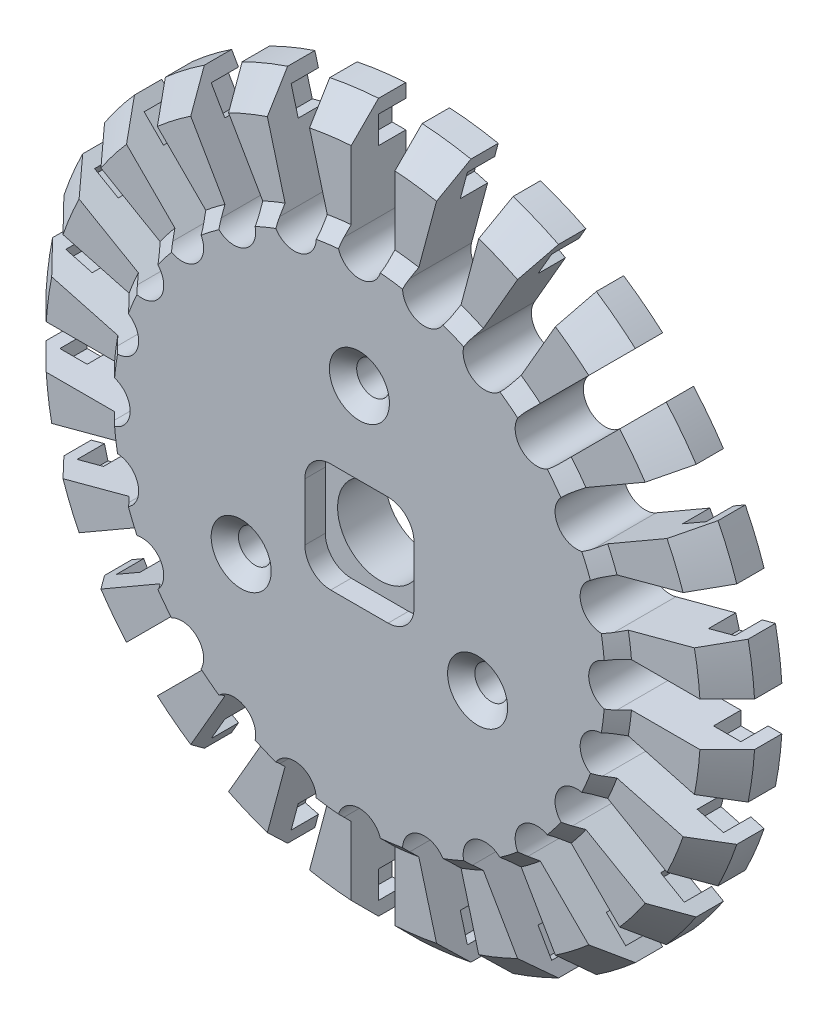
SolidWorks part; units mm, degrees
ref_plane "Plano frontal" through (0, 0, 0) normal (0, 0, 1) x (1, 0, 0)
ref_plane "Plano superior" through (0, 0, 0) normal (0, 1, 0) x (1, 0, 0)
ref_plane "Plano direito" through (0, 0, 0) normal (1, 0, 0) x (0, 0, -1)
sketch "Esboço1" plane through (0, 0, 0) normal (0, 0, 1) x (1, 0, 0)
  line L0 (0, 0) -> (26, 0) construction
  circle A0 centre (0, 0) radius 26
  dimension "R1" = 52
extrude "Ressalto-extrusão1" add sketch "Esboço1" along normal blind 4
fillet "Chanfro1" radius 2 1 edges at (26, 0, 4) type face fillet profile chamfer first side face at (26, 0, 4) second side face at (26, 0, 4)
sketch "Esboço3" plane through (0, 0, 0) normal (0, 0, -1) x (-1, 0, 0)
  line L0 (0, 0) -> (26, 0) construction
  line L1 (18.4, 1.6) -> (18.4, -1.6) construction
  line L2 (18.4, -1.6) -> (25.9507, -1.6)
  line L3 (18.4, 1.6) -> (25.9507, 1.6)
  line L4 (17.3589, -6.3078) -> (24.6524, -8.262)
  line L5 (18.1871, -3.2168) -> (25.4806, -5.1711)
  line L6 (0, 0) -> (25.1141, -6.7293) construction
  line L7 (15.1349, -10.5856) -> (21.674, -14.361)
  line L8 (16.7349, -7.8144) -> (23.274, -11.5897)
  line L9 (0, 0) -> (22.5167, -13) construction
  line L10 (11.8794, -14.1421) -> (17.2186, -19.4813)
  line L11 (14.1421, -11.8794) -> (19.4813, -17.2186)
  line L12 (0, 0) -> (18.3848, -18.3848) construction
  line L13 (7.8144, -16.7349) -> (11.5897, -23.274)
  line L14 (10.5856, -15.1349) -> (14.361, -21.674)
  line L15 (0, 0) -> (13, -22.5167) construction
  line L16 (3.2168, -18.1871) -> (5.1711, -25.4806)
  line L17 (6.3078, -17.3589) -> (8.262, -24.6524)
  line L18 (0, 0) -> (6.7293, -25.1141) construction
  line L19 (-1.6, -18.4) -> (-1.6, -25.9507)
  line L20 (1.6, -18.4) -> (1.6, -25.9507)
  line L21 (0, 0) -> (0, -26) construction
  line L22 (-6.3078, -17.3589) -> (-8.262, -24.6524)
  line L23 (-3.2168, -18.1871) -> (-5.1711, -25.4806)
  line L24 (0, 0) -> (-6.7293, -25.1141) construction
  line L25 (-10.5856, -15.1349) -> (-14.361, -21.674)
  line L26 (-7.8144, -16.7349) -> (-11.5897, -23.274)
  line L27 (0, 0) -> (-13, -22.5167) construction
  line L28 (-14.1421, -11.8794) -> (-19.4813, -17.2186)
  line L29 (-11.8794, -14.1421) -> (-17.2186, -19.4813)
  line L30 (0, 0) -> (-18.3848, -18.3848) construction
  line L31 (-16.7349, -7.8144) -> (-23.274, -11.5897)
  line L32 (-15.1349, -10.5856) -> (-21.674, -14.361)
  line L33 (0, 0) -> (-22.5167, -13) construction
  line L34 (-18.1871, -3.2168) -> (-25.4806, -5.1711)
  line L35 (-17.3589, -6.3078) -> (-24.6524, -8.262)
  line L36 (0, 0) -> (-25.1141, -6.7293) construction
  line L37 (-18.4, 1.6) -> (-25.9507, 1.6)
  line L38 (-18.4, -1.6) -> (-25.9507, -1.6)
  line L39 (0, 0) -> (-26, 0) construction
  line L40 (-17.3589, 6.3078) -> (-24.6524, 8.262)
  line L41 (-18.1871, 3.2168) -> (-25.4806, 5.1711)
  line L42 (0, 0) -> (-25.1141, 6.7293) construction
  line L43 (-15.1349, 10.5856) -> (-21.674, 14.361)
  line L44 (-16.7349, 7.8144) -> (-23.274, 11.5897)
  line L45 (0, 0) -> (-22.5167, 13) construction
  line L46 (-11.8794, 14.1421) -> (-17.2186, 19.4813)
  line L47 (-14.1421, 11.8794) -> (-19.4813, 17.2186)
  line L48 (0, 0) -> (-18.3848, 18.3848) construction
  line L49 (-7.8144, 16.7349) -> (-11.5897, 23.274)
  line L50 (-10.5856, 15.1349) -> (-14.361, 21.674)
  line L51 (0, 0) -> (-13, 22.5167) construction
  line L52 (-3.2168, 18.1871) -> (-5.1711, 25.4806)
  line L53 (-6.3078, 17.3589) -> (-8.262, 24.6524)
  line L54 (0, 0) -> (-6.7293, 25.1141) construction
  line L55 (1.6, 18.4) -> (1.6, 25.9507)
  line L56 (-1.6, 18.4) -> (-1.6, 25.9507)
  line L57 (0, 0) -> (0, 26) construction
  line L58 (6.3078, 17.3589) -> (8.262, 24.6524)
  line L59 (3.2168, 18.1871) -> (5.1711, 25.4806)
  line L60 (0, 0) -> (6.7293, 25.1141) construction
  line L61 (10.5856, 15.1349) -> (14.361, 21.674)
  line L62 (7.8144, 16.7349) -> (11.5897, 23.274)
  line L63 (0, 0) -> (13, 22.5167) construction
  line L64 (14.1421, 11.8794) -> (19.4813, 17.2186)
  line L65 (11.8794, 14.1421) -> (17.2186, 19.4813)
  line L66 (0, 0) -> (18.3848, 18.3848) construction
  line L67 (16.7349, 7.8144) -> (23.274, 11.5897)
  line L68 (15.1349, 10.5856) -> (21.674, 14.361)
  line L69 (0, 0) -> (22.5167, 13) construction
  line L70 (18.1871, 3.2168) -> (25.4806, 5.1711)
  line L71 (17.3589, 6.3078) -> (24.6524, 8.262)
  line L72 (0, 0) -> (25.1141, 6.7293) construction
  circle A0 centre (0, 0) radius 26 construction
  arc A1 (18.4, -1.6) -> (18.4, 1.6) centre (18.4, 0) cw
  arc A2 (25.9507, 1.6) -> (25.9507, -1.6) centre (0, 0) cw
  arc A3 (17.3589, -6.3078) -> (18.1871, -3.2168) centre (17.773, -4.7623) cw
  arc A4 (25.4806, -5.1711) -> (24.6524, -8.262) centre (0, 0) cw
  arc A5 (15.1349, -10.5856) -> (16.7349, -7.8144) centre (15.9349, -9.2) cw
  arc A6 (23.274, -11.5897) -> (21.674, -14.361) centre (0, 0) cw
  arc A7 (11.8794, -14.1421) -> (14.1421, -11.8794) centre (13.0108, -13.0108) cw
  arc A8 (19.4813, -17.2186) -> (17.2186, -19.4813) centre (0, 0) cw
  arc A9 (7.8144, -16.7349) -> (10.5856, -15.1349) centre (9.2, -15.9349) cw
  arc A10 (14.361, -21.674) -> (11.5897, -23.274) centre (0, 0) cw
  arc A11 (3.2168, -18.1871) -> (6.3078, -17.3589) centre (4.7623, -17.773) cw
  arc A12 (8.262, -24.6524) -> (5.1711, -25.4806) centre (0, 0) cw
  arc A13 (-1.6, -18.4) -> (1.6, -18.4) centre (0, -18.4) cw
  arc A14 (1.6, -25.9507) -> (-1.6, -25.9507) centre (0, 0) cw
  arc A15 (-6.3078, -17.3589) -> (-3.2168, -18.1871) centre (-4.7623, -17.773) cw
  arc A16 (-5.1711, -25.4806) -> (-8.262, -24.6524) centre (0, 0) cw
  arc A17 (-10.5856, -15.1349) -> (-7.8144, -16.7349) centre (-9.2, -15.9349) cw
  arc A18 (-11.5897, -23.274) -> (-14.361, -21.674) centre (0, 0) cw
  arc A19 (-14.1421, -11.8794) -> (-11.8794, -14.1421) centre (-13.0108, -13.0108) cw
  arc A20 (-17.2186, -19.4813) -> (-19.4813, -17.2186) centre (0, 0) cw
  arc A21 (-16.7349, -7.8144) -> (-15.1349, -10.5856) centre (-15.9349, -9.2) cw
  arc A22 (-21.674, -14.361) -> (-23.274, -11.5897) centre (0, 0) cw
  arc A23 (-18.1871, -3.2168) -> (-17.3589, -6.3078) centre (-17.773, -4.7623) cw
  arc A24 (-24.6524, -8.262) -> (-25.4806, -5.1711) centre (0, 0) cw
  arc A25 (-18.4, 1.6) -> (-18.4, -1.6) centre (-18.4, 0) cw
  arc A26 (-25.9507, -1.6) -> (-25.9507, 1.6) centre (0, 0) cw
  arc A27 (-17.3589, 6.3078) -> (-18.1871, 3.2168) centre (-17.773, 4.7623) cw
  arc A28 (-25.4806, 5.1711) -> (-24.6524, 8.262) centre (0, 0) cw
  arc A29 (-15.1349, 10.5856) -> (-16.7349, 7.8144) centre (-15.9349, 9.2) cw
  arc A30 (-23.274, 11.5897) -> (-21.674, 14.361) centre (0, 0) cw
  arc A31 (-11.8794, 14.1421) -> (-14.1421, 11.8794) centre (-13.0108, 13.0108) cw
  arc A32 (-19.4813, 17.2186) -> (-17.2186, 19.4813) centre (0, 0) cw
  arc A33 (-7.8144, 16.7349) -> (-10.5856, 15.1349) centre (-9.2, 15.9349) cw
  arc A34 (-14.361, 21.674) -> (-11.5897, 23.274) centre (0, 0) cw
  arc A35 (-3.2168, 18.1871) -> (-6.3078, 17.3589) centre (-4.7623, 17.773) cw
  arc A36 (-8.262, 24.6524) -> (-5.1711, 25.4806) centre (0, 0) cw
  arc A37 (1.6, 18.4) -> (-1.6, 18.4) centre (0, 18.4) cw
  arc A38 (-1.6, 25.9507) -> (1.6, 25.9507) centre (0, 0) cw
  arc A39 (6.3078, 17.3589) -> (3.2168, 18.1871) centre (4.7623, 17.773) cw
  arc A40 (5.1711, 25.4806) -> (8.262, 24.6524) centre (0, 0) cw
  arc A41 (10.5856, 15.1349) -> (7.8144, 16.7349) centre (9.2, 15.9349) cw
  arc A42 (11.5897, 23.274) -> (14.361, 21.674) centre (0, 0) cw
  arc A43 (14.1421, 11.8794) -> (11.8794, 14.1421) centre (13.0108, 13.0108) cw
  arc A44 (17.2186, 19.4813) -> (19.4813, 17.2186) centre (0, 0) cw
  arc A45 (16.7349, 7.8144) -> (15.1349, 10.5856) centre (15.9349, 9.2) cw
  arc A46 (21.674, 14.361) -> (23.274, 11.5897) centre (0, 0) cw
  arc A47 (18.1871, 3.2168) -> (17.3589, 6.3078) centre (17.773, 4.7623) cw
  arc A48 (24.6524, 8.262) -> (25.4806, 5.1711) centre (0, 0) cw
  point P9 (18.4, 0)
  point P20 (17.773, -4.7623)
  point P27 (15.9349, -9.2)
  point P34 (13.0108, -13.0108)
  point P41 (9.2, -15.9349)
  point P48 (4.7623, -17.773)
  point P55 (0, -18.4)
  point P62 (-4.7623, -17.773)
  point P69 (-9.2, -15.9349)
  point P76 (-13.0108, -13.0108)
  point P83 (-15.9349, -9.2)
  point P90 (-17.773, -4.7623)
  point P97 (-18.4, 0)
  point P104 (-17.773, 4.7623)
  point P111 (-15.9349, 9.2)
  point P118 (-13.0108, 13.0108)
  point P125 (-9.2, 15.9349)
  point P132 (-4.7623, 17.773)
  point P139 (0, 18.4)
  point P146 (4.7623, 17.773)
  point P153 (9.2, 15.9349)
  point P160 (13.0108, 13.0108)
  point P167 (15.9349, 9.2)
  point P174 (17.773, 4.7623)
  point P177 (0, 0)
  dimension "D1" = 3.2
  dimension "D2" = 7.6
  dimension "D3" = 24
extrude "Corte-extrusão1" cut sketch "Esboço3" against normal through all
sketch "Esboço4" plane through (0, 0, 0) normal (0, 0, -1) x (-1, 0, 0)
  line L0 (22.9466, 1.6) -> (22.9466, 2.6)
  line L1 (0, 0) -> (22.7165, -7.7433) construction
  line L2 (25.9507, 1.6) -> (18.4, 1.6) construction
  line L3 (0, 0) -> (23.5448, -4.6524) construction
  line L4 (18.4, -1.6) -> (25.9507, -1.6) construction
  line L5 (0, 0) -> (0, 6.1074) construction
  line L6 (0, 0) -> (23.9466, 1.6) construction
  line L7 (0, 0) -> (23.9466, -1.6) construction
  line L8 (0, 0) -> (19.9384, -13.3589) construction
  line L9 (0, 0) -> (21.5384, -10.5877) construction
  line L10 (0, 0) -> (15.8014, -18.0642) construction
  line L11 (0, 0) -> (18.0642, -15.8014) construction
  line L12 (0, 0) -> (10.5877, -21.5384) construction
  line L13 (0, 0) -> (13.3589, -19.9384) construction
  line L14 (0, 0) -> (4.6524, -23.5448) construction
  line L15 (0, 0) -> (7.7433, -22.7165) construction
  line L16 (0, 0) -> (-1.6, -23.9466) construction
  line L17 (0, 0) -> (1.6, -23.9466) construction
  line L18 (0, 0) -> (-7.7433, -22.7165) construction
  line L19 (0, 0) -> (-4.6524, -23.5448) construction
  line L20 (0, 0) -> (-13.3589, -19.9384) construction
  line L21 (0, 0) -> (-10.5877, -21.5384) construction
  line L22 (0, 0) -> (-18.0642, -15.8014) construction
  line L23 (0, 0) -> (-15.8014, -18.0642) construction
  line L24 (0, 0) -> (-21.5384, -10.5877) construction
  line L25 (0, 0) -> (-19.9384, -13.3589) construction
  line L26 (0, 0) -> (-23.5448, -4.6524) construction
  line L27 (0, 0) -> (-22.7165, -7.7433) construction
  line L28 (0, 0) -> (-23.9466, 1.6) construction
  line L29 (0, 0) -> (-23.9466, -1.6) construction
  line L30 (0, 0) -> (-22.7165, 7.7433) construction
  line L31 (0, 0) -> (-23.5448, 4.6524) construction
  line L32 (0, 0) -> (-19.9384, 13.3589) construction
  line L33 (0, 0) -> (-21.5384, 10.5877) construction
  line L34 (0, 0) -> (-15.8014, 18.0642) construction
  line L35 (0, 0) -> (-18.0642, 15.8014) construction
  line L36 (0, 0) -> (-10.5877, 21.5384) construction
  line L37 (0, 0) -> (-13.3589, 19.9384) construction
  line L38 (0, 0) -> (-4.6524, 23.5448) construction
  line L39 (0, 0) -> (-7.7433, 22.7165) construction
  line L40 (0, 0) -> (1.6, 23.9466) construction
  line L41 (0, 0) -> (-1.6, 23.9466) construction
  line L42 (0, 0) -> (7.7433, 22.7165) construction
  line L43 (0, 0) -> (4.6524, 23.5448) construction
  line L44 (0, 0) -> (13.3589, 19.9384) construction
  line L45 (0, 0) -> (10.5877, 21.5384) construction
  line L46 (0, 0) -> (18.0642, 15.8014) construction
  line L47 (0, 0) -> (15.8014, 18.0642) construction
  line L48 (0, 0) -> (21.5384, 10.5877) construction
  line L49 (0, 0) -> (19.9384, 13.3589) construction
  line L50 (0, 0) -> (23.5448, 4.6524) construction
  line L51 (0, 0) -> (22.7165, 7.7433) construction
  line L52 (22.9466, 2.6) -> (24.9466, 2.6)
  line L54 (0, 0) -> (0, 10) construction
  line L55 (24.9466, -2.6) -> (22.9466, -2.6)
  line L57 (23.9466, 1.6) -> (23.9466, -1.6) construction
  line L58 (22.9466, -1.6) -> (22.9466, -2.6)
  line L59 (22.9466, 2.6) -> (22.9466, -2.6) construction
  line L60 (24.9466, -2.6) -> (24.9466, 2.6) construction
  line L61 (24.9466, -2.6) -> (24.9466, -1.6)
  line L62 (24.9466, -1.6) -> (22.9466, -1.6)
  line L63 (24.9466, 1.6) -> (22.9466, 1.6)
  line L64 (24.9466, 1.6) -> (24.9466, 2.6)
  line L65 (22.5788, -4.3935) -> (22.8377, -3.4276)
  line L66 (22.8377, -3.4276) -> (24.7695, -3.9452)
  line L67 (23.4236, -8.9681) -> (21.4918, -8.4504)
  line L68 (21.7506, -7.4845) -> (21.4918, -8.4504)
  line L69 (23.4236, -8.9681) -> (23.6825, -8.0021)
  line L70 (23.6825, -8.0021) -> (21.7506, -7.4845)
  line L71 (24.5107, -4.9112) -> (22.5788, -4.3935)
  line L72 (24.5107, -4.9112) -> (24.7695, -3.9452)
  line L73 (0, 0) -> (23.5448, -4.6524) construction
  line L74 (0, 0) -> (22.7165, -7.7433) construction
  line L75 (22.8377, -3.4276) -> (21.4918, -8.4504) construction
  line L76 (23.4236, -8.9681) -> (24.7695, -3.9452) construction
  line L77 (20.6723, -10.0877) -> (21.1723, -9.2216)
  line L78 (21.1723, -9.2216) -> (22.9044, -10.2216)
  line L79 (20.3044, -14.725) -> (18.5723, -13.725)
  line L80 (19.0723, -12.8589) -> (18.5723, -13.725)
  line L81 (20.3044, -14.725) -> (20.8044, -13.8589)
  line L82 (20.8044, -13.8589) -> (19.0723, -12.8589)
  line L83 (22.4044, -11.0877) -> (20.6723, -10.0877)
  line L84 (22.4044, -11.0877) -> (22.9044, -10.2216)
  line L85 (0, 0) -> (21.5384, -10.5877) construction
  line L86 (0, 0) -> (19.9384, -13.3589) construction
  line L87 (21.1723, -9.2216) -> (18.5723, -13.725) construction
  line L88 (20.3044, -14.725) -> (22.9044, -10.2216) construction
  line L89 (17.3571, -15.0943) -> (18.0642, -14.3872)
  line L90 (18.0642, -14.3872) -> (19.4784, -15.8014)
  line L91 (15.8014, -19.4784) -> (14.3872, -18.0642)
  line L92 (15.0943, -17.3571) -> (14.3872, -18.0642)
  line L93 (15.8014, -19.4784) -> (16.5085, -18.7713)
  line L94 (16.5085, -18.7713) -> (15.0943, -17.3571)
  line L95 (18.7713, -16.5085) -> (17.3571, -15.0943)
  line L96 (18.7713, -16.5085) -> (19.4784, -15.8014)
  line L97 (0, 0) -> (18.0642, -15.8014) construction
  line L98 (0, 0) -> (15.8014, -18.0642) construction
  line L99 (18.0642, -14.3872) -> (14.3872, -18.0642) construction
  line L100 (15.8014, -19.4784) -> (19.4784, -15.8014) construction
  line L101 (12.8589, -19.0723) -> (13.725, -18.5723)
  line L102 (13.725, -18.5723) -> (14.725, -20.3044)
  line L103 (10.2216, -22.9044) -> (9.2216, -21.1723)
  line L104 (10.0877, -20.6723) -> (9.2216, -21.1723)
  line L105 (10.2216, -22.9044) -> (11.0877, -22.4044)
  line L106 (11.0877, -22.4044) -> (10.0877, -20.6723)
  line L107 (13.8589, -20.8044) -> (12.8589, -19.0723)
  line L108 (13.8589, -20.8044) -> (14.725, -20.3044)
  line L109 (0, 0) -> (13.3589, -19.9384) construction
  line L110 (0, 0) -> (10.5877, -21.5384) construction
  line L111 (13.725, -18.5723) -> (9.2216, -21.1723) construction
  line L112 (10.2216, -22.9044) -> (14.725, -20.3044) construction
  line L113 (7.4845, -21.7506) -> (8.4504, -21.4918)
  line L114 (8.4504, -21.4918) -> (8.9681, -23.4236)
  line L115 (3.9452, -24.7695) -> (3.4276, -22.8377)
  line L116 (4.3935, -22.5788) -> (3.4276, -22.8377)
  line L117 (3.9452, -24.7695) -> (4.9112, -24.5107)
  line L118 (4.9112, -24.5107) -> (4.3935, -22.5788)
  line L119 (8.0021, -23.6825) -> (7.4845, -21.7506)
  line L120 (8.0021, -23.6825) -> (8.9681, -23.4236)
  line L121 (0, 0) -> (7.7433, -22.7165) construction
  line L122 (0, 0) -> (4.6524, -23.5448) construction
  line L123 (8.4504, -21.4918) -> (3.4276, -22.8377) construction
  line L124 (3.9452, -24.7695) -> (8.9681, -23.4236) construction
  line L125 (1.6, -22.9466) -> (2.6, -22.9466)
  line L126 (2.6, -22.9466) -> (2.6, -24.9466)
  line L127 (-2.6, -24.9466) -> (-2.6, -22.9466)
  line L128 (-1.6, -22.9466) -> (-2.6, -22.9466)
  line L129 (-2.6, -24.9466) -> (-1.6, -24.9466)
  line L130 (-1.6, -24.9466) -> (-1.6, -22.9466)
  line L131 (1.6, -24.9466) -> (1.6, -22.9466)
  line L132 (1.6, -24.9466) -> (2.6, -24.9466)
  line L133 (0, 0) -> (1.6, -23.9466) construction
  line L134 (0, 0) -> (-1.6, -23.9466) construction
  line L135 (2.6, -22.9466) -> (-2.6, -22.9466) construction
  line L136 (-2.6, -24.9466) -> (2.6, -24.9466) construction
  line L137 (-4.3935, -22.5788) -> (-3.4276, -22.8377)
  line L138 (-3.4276, -22.8377) -> (-3.9452, -24.7695)
  line L139 (-8.9681, -23.4236) -> (-8.4504, -21.4918)
  line L140 (-7.4845, -21.7506) -> (-8.4504, -21.4918)
  line L141 (-8.9681, -23.4236) -> (-8.0021, -23.6825)
  line L142 (-8.0021, -23.6825) -> (-7.4845, -21.7506)
  line L143 (-4.9112, -24.5107) -> (-4.3935, -22.5788)
  line L144 (-4.9112, -24.5107) -> (-3.9452, -24.7695)
  line L145 (0, 0) -> (-4.6524, -23.5448) construction
  line L146 (0, 0) -> (-7.7433, -22.7165) construction
  line L147 (-3.4276, -22.8377) -> (-8.4504, -21.4918) construction
  line L148 (-8.9681, -23.4236) -> (-3.9452, -24.7695) construction
  line L149 (-10.0877, -20.6723) -> (-9.2216, -21.1723)
  line L150 (-9.2216, -21.1723) -> (-10.2216, -22.9044)
  line L151 (-14.725, -20.3044) -> (-13.725, -18.5723)
  line L152 (-12.8589, -19.0723) -> (-13.725, -18.5723)
  line L153 (-14.725, -20.3044) -> (-13.8589, -20.8044)
  line L154 (-13.8589, -20.8044) -> (-12.8589, -19.0723)
  line L155 (-11.0877, -22.4044) -> (-10.0877, -20.6723)
  line L156 (-11.0877, -22.4044) -> (-10.2216, -22.9044)
  line L157 (0, 0) -> (-10.5877, -21.5384) construction
  line L158 (0, 0) -> (-13.3589, -19.9384) construction
  line L159 (-9.2216, -21.1723) -> (-13.725, -18.5723) construction
  line L160 (-14.725, -20.3044) -> (-10.2216, -22.9044) construction
  line L161 (-15.0943, -17.3571) -> (-14.3872, -18.0642)
  line L162 (-14.3872, -18.0642) -> (-15.8014, -19.4784)
  line L163 (-19.4784, -15.8014) -> (-18.0642, -14.3872)
  line L164 (-17.3571, -15.0943) -> (-18.0642, -14.3872)
  line L165 (-19.4784, -15.8014) -> (-18.7713, -16.5085)
  line L166 (-18.7713, -16.5085) -> (-17.3571, -15.0943)
  line L167 (-16.5085, -18.7713) -> (-15.0943, -17.3571)
  line L168 (-16.5085, -18.7713) -> (-15.8014, -19.4784)
  line L169 (0, 0) -> (-15.8014, -18.0642) construction
  line L170 (0, 0) -> (-18.0642, -15.8014) construction
  line L171 (-14.3872, -18.0642) -> (-18.0642, -14.3872) construction
  line L172 (-19.4784, -15.8014) -> (-15.8014, -19.4784) construction
  line L173 (-19.0723, -12.8589) -> (-18.5723, -13.725)
  line L174 (-18.5723, -13.725) -> (-20.3044, -14.725)
  line L175 (-22.9044, -10.2216) -> (-21.1723, -9.2216)
  line L176 (-20.6723, -10.0877) -> (-21.1723, -9.2216)
  line L177 (-22.9044, -10.2216) -> (-22.4044, -11.0877)
  line L178 (-22.4044, -11.0877) -> (-20.6723, -10.0877)
  line L179 (-20.8044, -13.8589) -> (-19.0723, -12.8589)
  line L180 (-20.8044, -13.8589) -> (-20.3044, -14.725)
  line L181 (0, 0) -> (-19.9384, -13.3589) construction
  line L182 (0, 0) -> (-21.5384, -10.5877) construction
  line L183 (-18.5723, -13.725) -> (-21.1723, -9.2216) construction
  line L184 (-22.9044, -10.2216) -> (-20.3044, -14.725) construction
  line L185 (-21.7506, -7.4845) -> (-21.4918, -8.4504)
  line L186 (-21.4918, -8.4504) -> (-23.4236, -8.9681)
  line L187 (-24.7695, -3.9452) -> (-22.8377, -3.4276)
  line L188 (-22.5788, -4.3935) -> (-22.8377, -3.4276)
  line L189 (-24.7695, -3.9452) -> (-24.5107, -4.9112)
  line L190 (-24.5107, -4.9112) -> (-22.5788, -4.3935)
  line L191 (-23.6825, -8.0021) -> (-21.7506, -7.4845)
  line L192 (-23.6825, -8.0021) -> (-23.4236, -8.9681)
  line L193 (0, 0) -> (-22.7165, -7.7433) construction
  line L194 (0, 0) -> (-23.5448, -4.6524) construction
  line L195 (-21.4918, -8.4504) -> (-22.8377, -3.4276) construction
  line L196 (-24.7695, -3.9452) -> (-23.4236, -8.9681) construction
  line L197 (-22.9466, -1.6) -> (-22.9466, -2.6)
  line L198 (-22.9466, -2.6) -> (-24.9466, -2.6)
  line L199 (-24.9466, 2.6) -> (-22.9466, 2.6)
  line L200 (-22.9466, 1.6) -> (-22.9466, 2.6)
  line L201 (-24.9466, 2.6) -> (-24.9466, 1.6)
  line L202 (-24.9466, 1.6) -> (-22.9466, 1.6)
  line L203 (-24.9466, -1.6) -> (-22.9466, -1.6)
  line L204 (-24.9466, -1.6) -> (-24.9466, -2.6)
  line L205 (0, 0) -> (-23.9466, -1.6) construction
  line L206 (0, 0) -> (-23.9466, 1.6) construction
  line L207 (-22.9466, -2.6) -> (-22.9466, 2.6) construction
  line L208 (-24.9466, 2.6) -> (-24.9466, -2.6) construction
  line L209 (-22.5788, 4.3935) -> (-22.8377, 3.4276)
  line L210 (-22.8377, 3.4276) -> (-24.7695, 3.9452)
  line L211 (-23.4236, 8.9681) -> (-21.4918, 8.4504)
  line L212 (-21.7506, 7.4845) -> (-21.4918, 8.4504)
  line L213 (-23.4236, 8.9681) -> (-23.6825, 8.0021)
  line L214 (-23.6825, 8.0021) -> (-21.7506, 7.4845)
  line L215 (-24.5107, 4.9112) -> (-22.5788, 4.3935)
  line L216 (-24.5107, 4.9112) -> (-24.7695, 3.9452)
  line L217 (0, 0) -> (-23.5448, 4.6524) construction
  line L218 (0, 0) -> (-22.7165, 7.7433) construction
  line L219 (-22.8377, 3.4276) -> (-21.4918, 8.4504) construction
  line L220 (-23.4236, 8.9681) -> (-24.7695, 3.9452) construction
  line L221 (-20.6723, 10.0877) -> (-21.1723, 9.2216)
  line L222 (-21.1723, 9.2216) -> (-22.9044, 10.2216)
  line L223 (-20.3044, 14.725) -> (-18.5723, 13.725)
  line L224 (-19.0723, 12.8589) -> (-18.5723, 13.725)
  line L225 (-20.3044, 14.725) -> (-20.8044, 13.8589)
  line L226 (-20.8044, 13.8589) -> (-19.0723, 12.8589)
  line L227 (-22.4044, 11.0877) -> (-20.6723, 10.0877)
  line L228 (-22.4044, 11.0877) -> (-22.9044, 10.2216)
  line L229 (0, 0) -> (-21.5384, 10.5877) construction
  line L230 (0, 0) -> (-19.9384, 13.3589) construction
  line L231 (-21.1723, 9.2216) -> (-18.5723, 13.725) construction
  line L232 (-20.3044, 14.725) -> (-22.9044, 10.2216) construction
  line L233 (-17.3571, 15.0943) -> (-18.0642, 14.3872)
  line L234 (-18.0642, 14.3872) -> (-19.4784, 15.8014)
  line L235 (-15.8014, 19.4784) -> (-14.3872, 18.0642)
  line L236 (-15.0943, 17.3571) -> (-14.3872, 18.0642)
  line L237 (-15.8014, 19.4784) -> (-16.5085, 18.7713)
  line L238 (-16.5085, 18.7713) -> (-15.0943, 17.3571)
  line L239 (-18.7713, 16.5085) -> (-17.3571, 15.0943)
  line L240 (-18.7713, 16.5085) -> (-19.4784, 15.8014)
  line L241 (0, 0) -> (-18.0642, 15.8014) construction
  line L242 (0, 0) -> (-15.8014, 18.0642) construction
  line L243 (-18.0642, 14.3872) -> (-14.3872, 18.0642) construction
  line L244 (-15.8014, 19.4784) -> (-19.4784, 15.8014) construction
  line L245 (-12.8589, 19.0723) -> (-13.725, 18.5723)
  line L246 (-13.725, 18.5723) -> (-14.725, 20.3044)
  line L247 (-10.2216, 22.9044) -> (-9.2216, 21.1723)
  line L248 (-10.0877, 20.6723) -> (-9.2216, 21.1723)
  line L249 (-10.2216, 22.9044) -> (-11.0877, 22.4044)
  line L250 (-11.0877, 22.4044) -> (-10.0877, 20.6723)
  line L251 (-13.8589, 20.8044) -> (-12.8589, 19.0723)
  line L252 (-13.8589, 20.8044) -> (-14.725, 20.3044)
  line L253 (0, 0) -> (-13.3589, 19.9384) construction
  line L254 (0, 0) -> (-10.5877, 21.5384) construction
  line L255 (-13.725, 18.5723) -> (-9.2216, 21.1723) construction
  line L256 (-10.2216, 22.9044) -> (-14.725, 20.3044) construction
  line L257 (-7.4845, 21.7506) -> (-8.4504, 21.4918)
  line L258 (-8.4504, 21.4918) -> (-8.9681, 23.4236)
  line L259 (-3.9452, 24.7695) -> (-3.4276, 22.8377)
  line L260 (-4.3935, 22.5788) -> (-3.4276, 22.8377)
  line L261 (-3.9452, 24.7695) -> (-4.9112, 24.5107)
  line L262 (-4.9112, 24.5107) -> (-4.3935, 22.5788)
  line L263 (-8.0021, 23.6825) -> (-7.4845, 21.7506)
  line L264 (-8.0021, 23.6825) -> (-8.9681, 23.4236)
  line L265 (0, 0) -> (-7.7433, 22.7165) construction
  line L266 (0, 0) -> (-4.6524, 23.5448) construction
  line L267 (-8.4504, 21.4918) -> (-3.4276, 22.8377) construction
  line L268 (-3.9452, 24.7695) -> (-8.9681, 23.4236) construction
  line L269 (-1.6, 22.9466) -> (-2.6, 22.9466)
  line L270 (-2.6, 22.9466) -> (-2.6, 24.9466)
  line L271 (2.6, 24.9466) -> (2.6, 22.9466)
  line L272 (1.6, 22.9466) -> (2.6, 22.9466)
  line L273 (2.6, 24.9466) -> (1.6, 24.9466)
  line L274 (1.6, 24.9466) -> (1.6, 22.9466)
  line L275 (-1.6, 24.9466) -> (-1.6, 22.9466)
  line L276 (-1.6, 24.9466) -> (-2.6, 24.9466)
  line L277 (0, 0) -> (-1.6, 23.9466) construction
  line L278 (0, 0) -> (1.6, 23.9466) construction
  line L279 (-2.6, 22.9466) -> (2.6, 22.9466) construction
  line L280 (2.6, 24.9466) -> (-2.6, 24.9466) construction
  line L281 (4.3935, 22.5788) -> (3.4276, 22.8377)
  line L282 (3.4276, 22.8377) -> (3.9452, 24.7695)
  line L283 (8.9681, 23.4236) -> (8.4504, 21.4918)
  line L284 (7.4845, 21.7506) -> (8.4504, 21.4918)
  line L285 (8.9681, 23.4236) -> (8.0021, 23.6825)
  line L286 (8.0021, 23.6825) -> (7.4845, 21.7506)
  line L287 (4.9112, 24.5107) -> (4.3935, 22.5788)
  line L288 (4.9112, 24.5107) -> (3.9452, 24.7695)
  line L289 (0, 0) -> (4.6524, 23.5448) construction
  line L290 (0, 0) -> (7.7433, 22.7165) construction
  line L291 (3.4276, 22.8377) -> (8.4504, 21.4918) construction
  line L292 (8.9681, 23.4236) -> (3.9452, 24.7695) construction
  line L293 (10.0877, 20.6723) -> (9.2216, 21.1723)
  line L294 (9.2216, 21.1723) -> (10.2216, 22.9044)
  line L295 (14.725, 20.3044) -> (13.725, 18.5723)
  line L296 (12.8589, 19.0723) -> (13.725, 18.5723)
  line L297 (14.725, 20.3044) -> (13.8589, 20.8044)
  line L298 (13.8589, 20.8044) -> (12.8589, 19.0723)
  line L299 (11.0877, 22.4044) -> (10.0877, 20.6723)
  line L300 (11.0877, 22.4044) -> (10.2216, 22.9044)
  line L301 (0, 0) -> (10.5877, 21.5384) construction
  line L302 (0, 0) -> (13.3589, 19.9384) construction
  line L303 (9.2216, 21.1723) -> (13.725, 18.5723) construction
  line L304 (14.725, 20.3044) -> (10.2216, 22.9044) construction
  line L305 (15.0943, 17.3571) -> (14.3872, 18.0642)
  line L306 (14.3872, 18.0642) -> (15.8014, 19.4784)
  line L307 (19.4784, 15.8014) -> (18.0642, 14.3872)
  line L308 (17.3571, 15.0943) -> (18.0642, 14.3872)
  line L309 (19.4784, 15.8014) -> (18.7713, 16.5085)
  line L310 (18.7713, 16.5085) -> (17.3571, 15.0943)
  line L311 (16.5085, 18.7713) -> (15.0943, 17.3571)
  line L312 (16.5085, 18.7713) -> (15.8014, 19.4784)
  line L313 (0, 0) -> (15.8014, 18.0642) construction
  line L314 (0, 0) -> (18.0642, 15.8014) construction
  line L315 (14.3872, 18.0642) -> (18.0642, 14.3872) construction
  line L316 (19.4784, 15.8014) -> (15.8014, 19.4784) construction
  line L317 (19.0723, 12.8589) -> (18.5723, 13.725)
  line L318 (18.5723, 13.725) -> (20.3044, 14.725)
  line L319 (22.9044, 10.2216) -> (21.1723, 9.2216)
  line L320 (20.6723, 10.0877) -> (21.1723, 9.2216)
  line L321 (22.9044, 10.2216) -> (22.4044, 11.0877)
  line L322 (22.4044, 11.0877) -> (20.6723, 10.0877)
  line L323 (20.8044, 13.8589) -> (19.0723, 12.8589)
  line L324 (20.8044, 13.8589) -> (20.3044, 14.725)
  line L325 (0, 0) -> (19.9384, 13.3589) construction
  line L326 (0, 0) -> (21.5384, 10.5877) construction
  line L327 (18.5723, 13.725) -> (21.1723, 9.2216) construction
  line L328 (22.9044, 10.2216) -> (20.3044, 14.725) construction
  line L329 (21.7506, 7.4845) -> (21.4918, 8.4504)
  line L330 (21.4918, 8.4504) -> (23.4236, 8.9681)
  line L331 (24.7695, 3.9452) -> (22.8377, 3.4276)
  line L332 (22.5788, 4.3935) -> (22.8377, 3.4276)
  line L333 (24.7695, 3.9452) -> (24.5107, 4.9112)
  line L334 (24.5107, 4.9112) -> (22.5788, 4.3935)
  line L335 (23.6825, 8.0021) -> (21.7506, 7.4845)
  line L336 (23.6825, 8.0021) -> (23.4236, 8.9681)
  line L337 (0, 0) -> (22.7165, 7.7433) construction
  line L338 (0, 0) -> (23.5448, 4.6524) construction
  line L339 (21.4918, 8.4504) -> (22.8377, 3.4276) construction
  line L340 (24.7695, 3.9452) -> (23.4236, 8.9681) construction
  line L341 (0, 0) -> (8.6603, -5) construction
  line L342 (0, 0) -> (-8.6603, -5) construction
  point P5 (22.7165, -7.7433)
  point P8 (23.9466, 1.6)
  point P11 (23.9466, -1.6)
  point P13 (22.9466, -1.6)
  point P20 (19.9384, -13.3589)
  point P23 (15.8014, -18.0642)
  point P26 (10.5877, -21.5384)
  point P29 (4.6524, -23.5448)
  point P32 (-1.6, -23.9466)
  point P35 (-7.7433, -22.7165)
  point P38 (-13.3589, -19.9384)
  point P41 (-18.0642, -15.8014)
  point P44 (-21.5384, -10.5877)
  point P47 (-23.5448, -4.6524)
  point P50 (-23.9466, 1.6)
  point P53 (-22.7165, 7.7433)
  point P56 (-19.9384, 13.3589)
  point P59 (-15.8014, 18.0642)
  point P62 (-10.5877, 21.5384)
  point P65 (-4.6524, 23.5448)
  point P68 (1.6, 23.9466)
  point P71 (7.7433, 22.7165)
  point P74 (13.3589, 19.9384)
  point P77 (18.0642, 15.8014)
  point P80 (21.5384, 10.5877)
  point P83 (23.5448, 4.6524)
  point P86 (0, 0)
  point P90 (0, 0)
  point P93 (24.9466, -1.6)
  point P94 (24.9466, 1.6)
  point P95 (24.9466, 1.6)
  point P98 (23.9466, 2.6)
  point P108 (23.5448, -4.6524)
  point P109 (22.7165, -7.7433)
  point P110 (21.7506, -7.4845)
  point P115 (23.6825, -8.0021)
  point P116 (24.5107, -4.9112)
  point P117 (24.5107, -4.9112)
  point P124 (21.5384, -10.5877)
  point P125 (19.9384, -13.3589)
  point P126 (19.0723, -12.8589)
  point P131 (20.8044, -13.8589)
  point P132 (22.4044, -11.0877)
  point P133 (22.4044, -11.0877)
  point P140 (18.0642, -15.8014)
  point P141 (15.8014, -18.0642)
  point P142 (15.0943, -17.3571)
  point P147 (16.5085, -18.7713)
  point P148 (18.7713, -16.5085)
  point P149 (18.7713, -16.5085)
  point P156 (13.3589, -19.9384)
  point P157 (10.5877, -21.5384)
  point P158 (10.0877, -20.6723)
  point P163 (11.0877, -22.4044)
  point P164 (13.8589, -20.8044)
  point P165 (13.8589, -20.8044)
  point P172 (7.7433, -22.7165)
  point P173 (4.6524, -23.5448)
  point P174 (4.3935, -22.5788)
  point P179 (4.9112, -24.5107)
  point P180 (8.0021, -23.6825)
  point P181 (8.0021, -23.6825)
  point P188 (1.6, -23.9466)
  point P189 (-1.6, -23.9466)
  point P190 (-1.6, -22.9466)
  point P195 (-1.6, -24.9466)
  point P196 (1.6, -24.9466)
  point P197 (1.6, -24.9466)
  point P204 (-4.6524, -23.5448)
  point P205 (-7.7433, -22.7165)
  point P206 (-7.4845, -21.7506)
  point P211 (-8.0021, -23.6825)
  point P212 (-4.9112, -24.5107)
  point P213 (-4.9112, -24.5107)
  point P220 (-10.5877, -21.5384)
  point P221 (-13.3589, -19.9384)
  point P222 (-12.8589, -19.0723)
  point P227 (-13.8589, -20.8044)
  point P228 (-11.0877, -22.4044)
  point P229 (-11.0877, -22.4044)
  point P236 (-15.8014, -18.0642)
  point P237 (-18.0642, -15.8014)
  point P238 (-17.3571, -15.0943)
  point P243 (-18.7713, -16.5085)
  point P244 (-16.5085, -18.7713)
  point P245 (-16.5085, -18.7713)
  point P252 (-19.9384, -13.3589)
  point P253 (-21.5384, -10.5877)
  point P254 (-20.6723, -10.0877)
  point P259 (-22.4044, -11.0877)
  point P260 (-20.8044, -13.8589)
  point P261 (-20.8044, -13.8589)
  point P268 (-22.7165, -7.7433)
  point P269 (-23.5448, -4.6524)
  point P270 (-22.5788, -4.3935)
  point P275 (-24.5107, -4.9112)
  point P276 (-23.6825, -8.0021)
  point P277 (-23.6825, -8.0021)
  point P284 (-23.9466, -1.6)
  point P285 (-23.9466, 1.6)
  point P286 (-22.9466, 1.6)
  point P291 (-24.9466, 1.6)
  point P292 (-24.9466, -1.6)
  point P293 (-24.9466, -1.6)
  point P300 (-23.5448, 4.6524)
  point P301 (-22.7165, 7.7433)
  point P302 (-21.7506, 7.4845)
  point P307 (-23.6825, 8.0021)
  point P308 (-24.5107, 4.9112)
  point P309 (-24.5107, 4.9112)
  point P316 (-21.5384, 10.5877)
  point P317 (-19.9384, 13.3589)
  point P318 (-19.0723, 12.8589)
  point P323 (-20.8044, 13.8589)
  point P324 (-22.4044, 11.0877)
  point P325 (-22.4044, 11.0877)
  point P332 (-18.0642, 15.8014)
  point P333 (-15.8014, 18.0642)
  point P334 (-15.0943, 17.3571)
  point P339 (-16.5085, 18.7713)
  point P340 (-18.7713, 16.5085)
  point P341 (-18.7713, 16.5085)
  point P348 (-13.3589, 19.9384)
  point P349 (-10.5877, 21.5384)
  point P350 (-10.0877, 20.6723)
  point P355 (-11.0877, 22.4044)
  point P356 (-13.8589, 20.8044)
  point P357 (-13.8589, 20.8044)
  point P364 (-7.7433, 22.7165)
  point P365 (-4.6524, 23.5448)
  point P366 (-4.3935, 22.5788)
  point P371 (-4.9112, 24.5107)
  point P372 (-8.0021, 23.6825)
  point P373 (-8.0021, 23.6825)
  point P380 (-1.6, 23.9466)
  point P381 (1.6, 23.9466)
  point P382 (1.6, 22.9466)
  point P387 (1.6, 24.9466)
  point P388 (-1.6, 24.9466)
  point P389 (-1.6, 24.9466)
  point P396 (4.6524, 23.5448)
  point P397 (7.7433, 22.7165)
  point P398 (7.4845, 21.7506)
  point P403 (8.0021, 23.6825)
  point P404 (4.9112, 24.5107)
  point P405 (4.9112, 24.5107)
  point P412 (10.5877, 21.5384)
  point P413 (13.3589, 19.9384)
  point P414 (12.8589, 19.0723)
  point P419 (13.8589, 20.8044)
  point P420 (11.0877, 22.4044)
  point P421 (11.0877, 22.4044)
  point P428 (15.8014, 18.0642)
  point P429 (18.0642, 15.8014)
  point P430 (17.3571, 15.0943)
  point P435 (18.7713, 16.5085)
  point P436 (16.5085, 18.7713)
  point P437 (16.5085, 18.7713)
  point P444 (19.9384, 13.3589)
  point P445 (21.5384, 10.5877)
  point P446 (20.6723, 10.0877)
  point P451 (22.4044, 11.0877)
  point P452 (20.8044, 13.8589)
  point P453 (20.8044, 13.8589)
  point P460 (22.7165, 7.7433)
  point P461 (23.5448, 4.6524)
  point P462 (22.5788, 4.3935)
  point P467 (24.5107, 4.9112)
  point P468 (23.6825, 8.0021)
  point P469 (23.6825, 8.0021)
  point P473 (0, 0)
  point P475 (0, 0)
  dimension "D1" = 24
  dimension "D2" = 2
  dimension "D3" = 24
  dimension "D4" = 1
  dimension "D5" = 10
  dimension "D6" = 24
sketch "Esboço8" plane through (0, 0, 4) normal (0, 0, 1) x (1, 0, 0)
  circle A0 centre (0, 0) radius 19
  dimension "D1" = 38
extrude "Ressalto-extrusão2" add sketch "Esboço8" along normal blind 1
sketch "Esboço11" plane through (0, 0, 5) normal (0, 0, 1) x (1, 0, 0)
  circle A0 centre (0, 0) radius 3.1
  dimension "D1" = 6.2
extrude "Corte-extrusão3" cut sketch "Esboço11" against normal through all
chamfer "Chanfro4" distance 1 1 edges at (19, 0, 5)
extrude "Corte-extrusão4" cut sketch "Esboço4" against normal blind 2
sketch "Esboço18" plane through (0, 0, 5) normal (0, 0, 1) x (1, 0, 0)
  line L0 (0, 0) -> (0, 10) construction
  line L1 (0, 0) -> (-8.6603, -5) construction
  line L2 (0, 0) -> (8.6603, -5) construction
  line L3 (0, 0) -> (-2.48, 18.8375)
  arc A0 (-1.6, 18.9325) -> (-3.3546, 18.7015) centre (0, 0) ccw construction
  arc A1 (-1.6, 18.9325) -> (-3.3546, 18.7015) centre (0, 0) ccw
ref_plane "Plano3" through (-1.6, 0, 0) normal (1, 0, 0) x (0, 0, -1)
sketch "Esboço21" plane through (-1.6, 0, 0) normal (1, 0, 0) x (0, 0, -1)
  line L0 (0, 22.9466) -> (-2, 24.9466) construction
  line L1 (-2, 24.9466) -> (0, 24.9466) construction
  circle A1 centre (-1, 23.9466) radius 1
  circle A2 centre (-1, 23.9466) radius 5
  dimension "D1" = 10
sketch "Esboço31" plane through (0, 0, 4) normal (0, 0, -1) x (-1, 0, 0)
  line L240 (25.9507, -1.6) -> (24.9466, -1.6)
  line L241 (24.9466, -1.6) -> (24.9466, -2.6)
  line L242 (24.9466, -1.6) -> (24.9466, -2.6)
  line L243 (24.9466, -2.6) -> (22.9466, -2.6)
  line L244 (24.9466, -2.6) -> (22.9466, -2.6)
  line L245 (18.4, 1.6) -> (22.9466, 1.6)
  line L246 (22.9466, -2.6) -> (22.9466, -1.6)
  line L247 (22.9466, -2.6) -> (22.9466, -1.6)
  line L248 (22.9466, -1.6) -> (18.4, -1.6)
  line L249 (22.9466, -1.6) -> (18.4, -1.6)
  line L250 (25.4806, 5.1711) -> (24.5107, 4.9112)
  line L251 (22.9466, 1.6) -> (22.9466, 2.6)
  line L252 (22.9466, 1.6) -> (22.9466, 2.6)
  line L253 (22.9466, 2.6) -> (24.9466, 2.6)
  line L254 (22.9466, 2.6) -> (24.9466, 2.6)
  line L255 (17.3589, 6.3078) -> (21.7506, 7.4845)
  line L256 (24.9466, 2.6) -> (24.9466, 1.6)
  line L257 (24.9466, 2.6) -> (24.9466, 1.6)
  line L258 (24.9466, 1.6) -> (25.9507, 1.6)
  line L259 (24.9466, 1.6) -> (25.9507, 1.6)
  line L260 (23.274, 11.5897) -> (22.4044, 11.0877)
  line L261 (24.5107, 4.9112) -> (24.7695, 3.9452)
  line L262 (24.5107, 4.9112) -> (24.7695, 3.9452)
  line L263 (24.7695, 3.9452) -> (22.8377, 3.4276)
  line L264 (24.7695, 3.9452) -> (22.8377, 3.4276)
  line L265 (15.1349, 10.5856) -> (19.0723, 12.8589)
  line L266 (22.8377, 3.4276) -> (22.5788, 4.3935)
  line L267 (22.8377, 3.4276) -> (22.5788, 4.3935)
  line L268 (22.5788, 4.3935) -> (18.1871, 3.2168)
  line L269 (22.5788, 4.3935) -> (18.1871, 3.2168)
  line L270 (19.4813, 17.2186) -> (18.7713, 16.5085)
  line L271 (21.7506, 7.4845) -> (21.4918, 8.4504)
  line L272 (21.7506, 7.4845) -> (21.4918, 8.4504)
  line L273 (21.4918, 8.4504) -> (23.4236, 8.9681)
  line L274 (21.4918, 8.4504) -> (23.4236, 8.9681)
  line L275 (11.8794, 14.1421) -> (15.0943, 17.3571)
  line L276 (23.4236, 8.9681) -> (23.6825, 8.0021)
  line L277 (23.4236, 8.9681) -> (23.6825, 8.0021)
  line L278 (23.6825, 8.0021) -> (24.6524, 8.262)
  line L279 (23.6825, 8.0021) -> (24.6524, 8.262)
  line L280 (14.361, 21.674) -> (13.8589, 20.8044)
  line L281 (22.4044, 11.0877) -> (22.9044, 10.2216)
  line L282 (22.4044, 11.0877) -> (22.9044, 10.2216)
  line L283 (22.9044, 10.2216) -> (21.1723, 9.2216)
  line L284 (22.9044, 10.2216) -> (21.1723, 9.2216)
  line L285 (7.8144, 16.7349) -> (10.0877, 20.6723)
  line L286 (21.1723, 9.2216) -> (20.6723, 10.0877)
  line L287 (21.1723, 9.2216) -> (20.6723, 10.0877)
  line L288 (20.6723, 10.0877) -> (16.7349, 7.8144)
  line L289 (20.6723, 10.0877) -> (16.7349, 7.8144)
  line L290 (8.262, 24.6524) -> (8.0021, 23.6825)
  line L291 (19.0723, 12.8589) -> (18.5723, 13.725)
  line L292 (19.0723, 12.8589) -> (18.5723, 13.725)
  line L293 (18.5723, 13.725) -> (20.3044, 14.725)
  line L294 (18.5723, 13.725) -> (20.3044, 14.725)
  line L295 (3.2168, 18.1871) -> (4.3935, 22.5788)
  line L296 (20.3044, 14.725) -> (20.8044, 13.8589)
  line L297 (20.3044, 14.725) -> (20.8044, 13.8589)
  line L298 (20.8044, 13.8589) -> (21.674, 14.361)
  line L299 (20.8044, 13.8589) -> (21.674, 14.361)
  line L300 (1.6, 25.9507) -> (1.6, 24.9466)
  line L301 (18.7713, 16.5085) -> (19.4784, 15.8014)
  line L302 (18.7713, 16.5085) -> (19.4784, 15.8014)
  line L303 (19.4784, 15.8014) -> (18.0642, 14.3872)
  line L304 (19.4784, 15.8014) -> (18.0642, 14.3872)
  line L305 (-1.6, 18.4) -> (-1.6, 22.9466)
  line L306 (18.0642, 14.3872) -> (17.3571, 15.0943)
  line L307 (18.0642, 14.3872) -> (17.3571, 15.0943)
  line L308 (17.3571, 15.0943) -> (14.1421, 11.8794)
  line L309 (17.3571, 15.0943) -> (14.1421, 11.8794)
  line L310 (-5.1711, 25.4806) -> (-4.9112, 24.5107)
  line L311 (15.0943, 17.3571) -> (14.3872, 18.0642)
  line L312 (15.0943, 17.3571) -> (14.3872, 18.0642)
  line L313 (14.3872, 18.0642) -> (15.8014, 19.4784)
  line L314 (14.3872, 18.0642) -> (15.8014, 19.4784)
  line L315 (-6.3078, 17.3589) -> (-7.4845, 21.7506)
  line L316 (15.8014, 19.4784) -> (16.5085, 18.7713)
  line L317 (15.8014, 19.4784) -> (16.5085, 18.7713)
  line L318 (16.5085, 18.7713) -> (17.2186, 19.4813)
  line L319 (16.5085, 18.7713) -> (17.2186, 19.4813)
  line L320 (-11.5897, 23.274) -> (-11.0877, 22.4044)
  line L321 (13.8589, 20.8044) -> (14.725, 20.3044)
  line L322 (13.8589, 20.8044) -> (14.725, 20.3044)
  line L323 (14.725, 20.3044) -> (13.725, 18.5723)
  line L324 (14.725, 20.3044) -> (13.725, 18.5723)
  line L325 (-10.5856, 15.1349) -> (-12.8589, 19.0723)
  line L326 (13.725, 18.5723) -> (12.8589, 19.0723)
  line L327 (13.725, 18.5723) -> (12.8589, 19.0723)
  line L328 (12.8589, 19.0723) -> (10.5856, 15.1349)
  line L329 (12.8589, 19.0723) -> (10.5856, 15.1349)
  line L330 (-17.2186, 19.4813) -> (-16.5085, 18.7713)
  line L331 (10.0877, 20.6723) -> (9.2216, 21.1723)
  line L332 (10.0877, 20.6723) -> (9.2216, 21.1723)
  line L333 (9.2216, 21.1723) -> (10.2216, 22.9044)
  line L334 (9.2216, 21.1723) -> (10.2216, 22.9044)
  line L335 (-14.1421, 11.8794) -> (-17.3571, 15.0943)
  line L336 (10.2216, 22.9044) -> (11.0877, 22.4044)
  line L337 (10.2216, 22.9044) -> (11.0877, 22.4044)
  line L338 (11.0877, 22.4044) -> (11.5897, 23.274)
  line L339 (11.0877, 22.4044) -> (11.5897, 23.274)
  line L340 (-21.674, 14.361) -> (-20.8044, 13.8589)
  line L341 (8.0021, 23.6825) -> (8.9681, 23.4236)
  line L342 (8.0021, 23.6825) -> (8.9681, 23.4236)
  line L343 (8.9681, 23.4236) -> (8.4504, 21.4918)
  line L344 (8.9681, 23.4236) -> (8.4504, 21.4918)
  line L345 (-16.7349, 7.8144) -> (-20.6723, 10.0877)
  line L346 (8.4504, 21.4918) -> (7.4845, 21.7506)
  line L347 (8.4504, 21.4918) -> (7.4845, 21.7506)
  line L348 (7.4845, 21.7506) -> (6.3078, 17.3589)
  line L349 (7.4845, 21.7506) -> (6.3078, 17.3589)
  line L350 (-24.6524, 8.262) -> (-23.6825, 8.0021)
  line L351 (4.3935, 22.5788) -> (3.4276, 22.8377)
  line L352 (4.3935, 22.5788) -> (3.4276, 22.8377)
  line L353 (3.4276, 22.8377) -> (3.9452, 24.7695)
  line L354 (3.4276, 22.8377) -> (3.9452, 24.7695)
  line L355 (-18.1871, 3.2168) -> (-22.5788, 4.3935)
  line L356 (3.9452, 24.7695) -> (4.9112, 24.5107)
  line L357 (3.9452, 24.7695) -> (4.9112, 24.5107)
  line L358 (4.9112, 24.5107) -> (5.1711, 25.4806)
  line L359 (4.9112, 24.5107) -> (5.1711, 25.4806)
  line L360 (-25.9507, 1.6) -> (-24.9466, 1.6)
  line L361 (1.6, 24.9466) -> (2.6, 24.9466)
  line L362 (1.6, 24.9466) -> (2.6, 24.9466)
  line L363 (2.6, 24.9466) -> (2.6, 22.9466)
  line L364 (2.6, 24.9466) -> (2.6, 22.9466)
  line L365 (-18.4, -1.6) -> (-22.9466, -1.6)
  line L366 (2.6, 22.9466) -> (1.6, 22.9466)
  line L367 (2.6, 22.9466) -> (1.6, 22.9466)
  line L368 (1.6, 22.9466) -> (1.6, 18.4)
  line L369 (1.6, 22.9466) -> (1.6, 18.4)
  line L370 (-25.4806, -5.1711) -> (-24.5107, -4.9112)
  line L371 (-1.6, 22.9466) -> (-2.6, 22.9466)
  line L372 (-1.6, 22.9466) -> (-2.6, 22.9466)
  line L373 (-2.6, 22.9466) -> (-2.6, 24.9466)
  line L374 (-2.6, 22.9466) -> (-2.6, 24.9466)
  line L375 (-17.3589, -6.3078) -> (-21.7506, -7.4845)
  line L376 (-2.6, 24.9466) -> (-1.6, 24.9466)
  line L377 (-2.6, 24.9466) -> (-1.6, 24.9466)
  line L378 (-1.6, 24.9466) -> (-1.6, 25.9507)
  line L379 (-1.6, 24.9466) -> (-1.6, 25.9507)
  line L380 (-23.274, -11.5897) -> (-22.4044, -11.0877)
  line L381 (-4.9112, 24.5107) -> (-3.9452, 24.7695)
  line L382 (-4.9112, 24.5107) -> (-3.9452, 24.7695)
  line L383 (-3.9452, 24.7695) -> (-3.4276, 22.8377)
  line L384 (-3.9452, 24.7695) -> (-3.4276, 22.8377)
  line L385 (-15.1349, -10.5856) -> (-19.0723, -12.8589)
  line L386 (-3.4276, 22.8377) -> (-4.3935, 22.5788)
  line L387 (-3.4276, 22.8377) -> (-4.3935, 22.5788)
  line L388 (-4.3935, 22.5788) -> (-3.2168, 18.1871)
  line L389 (-4.3935, 22.5788) -> (-3.2168, 18.1871)
  line L390 (-19.4813, -17.2186) -> (-18.7713, -16.5085)
  line L391 (-7.4845, 21.7506) -> (-8.4504, 21.4918)
  line L392 (-7.4845, 21.7506) -> (-8.4504, 21.4918)
  line L393 (-8.4504, 21.4918) -> (-8.9681, 23.4236)
  line L394 (-8.4504, 21.4918) -> (-8.9681, 23.4236)
  line L395 (-11.8794, -14.1421) -> (-15.0943, -17.3571)
  line L396 (-8.9681, 23.4236) -> (-8.0021, 23.6825)
  line L397 (-8.9681, 23.4236) -> (-8.0021, 23.6825)
  line L398 (-8.0021, 23.6825) -> (-8.262, 24.6524)
  line L399 (-8.0021, 23.6825) -> (-8.262, 24.6524)
  line L400 (-14.361, -21.674) -> (-13.8589, -20.8044)
  line L401 (-11.0877, 22.4044) -> (-10.2216, 22.9044)
  line L402 (-11.0877, 22.4044) -> (-10.2216, 22.9044)
  line L403 (-10.2216, 22.9044) -> (-9.2216, 21.1723)
  line L404 (-10.2216, 22.9044) -> (-9.2216, 21.1723)
  line L405 (-7.8144, -16.7349) -> (-10.0877, -20.6723)
  line L406 (-9.2216, 21.1723) -> (-10.0877, 20.6723)
  line L407 (-9.2216, 21.1723) -> (-10.0877, 20.6723)
  line L408 (-10.0877, 20.6723) -> (-7.8144, 16.7349)
  line L409 (-10.0877, 20.6723) -> (-7.8144, 16.7349)
  line L410 (-8.262, -24.6524) -> (-8.0021, -23.6825)
  line L411 (-12.8589, 19.0723) -> (-13.725, 18.5723)
  line L412 (-12.8589, 19.0723) -> (-13.725, 18.5723)
  line L413 (-13.725, 18.5723) -> (-14.725, 20.3044)
  line L414 (-13.725, 18.5723) -> (-14.725, 20.3044)
  line L415 (-3.2168, -18.1871) -> (-4.3935, -22.5788)
  line L416 (-14.725, 20.3044) -> (-13.8589, 20.8044)
  line L417 (-14.725, 20.3044) -> (-13.8589, 20.8044)
  line L418 (-13.8589, 20.8044) -> (-14.361, 21.674)
  line L419 (-13.8589, 20.8044) -> (-14.361, 21.674)
  line L420 (-1.6, -25.9507) -> (-1.6, -24.9466)
  line L421 (-16.5085, 18.7713) -> (-15.8014, 19.4784)
  line L422 (-16.5085, 18.7713) -> (-15.8014, 19.4784)
  line L423 (-15.8014, 19.4784) -> (-14.3872, 18.0642)
  line L424 (-15.8014, 19.4784) -> (-14.3872, 18.0642)
  line L425 (1.6, -18.4) -> (1.6, -22.9466)
  line L426 (-14.3872, 18.0642) -> (-15.0943, 17.3571)
  line L427 (-14.3872, 18.0642) -> (-15.0943, 17.3571)
  line L428 (-15.0943, 17.3571) -> (-11.8794, 14.1421)
  line L429 (-15.0943, 17.3571) -> (-11.8794, 14.1421)
  line L430 (5.1711, -25.4806) -> (4.9112, -24.5107)
  line L431 (-17.3571, 15.0943) -> (-18.0642, 14.3872)
  line L432 (-17.3571, 15.0943) -> (-18.0642, 14.3872)
  line L433 (-18.0642, 14.3872) -> (-19.4784, 15.8014)
  line L434 (-18.0642, 14.3872) -> (-19.4784, 15.8014)
  line L435 (6.3078, -17.3589) -> (7.4845, -21.7506)
  line L436 (-19.4784, 15.8014) -> (-18.7713, 16.5085)
  line L437 (-19.4784, 15.8014) -> (-18.7713, 16.5085)
  line L438 (-18.7713, 16.5085) -> (-19.4813, 17.2186)
  line L439 (-18.7713, 16.5085) -> (-19.4813, 17.2186)
  line L440 (11.5897, -23.274) -> (11.0877, -22.4044)
  line L441 (-20.8044, 13.8589) -> (-20.3044, 14.725)
  line L442 (-20.8044, 13.8589) -> (-20.3044, 14.725)
  line L443 (-20.3044, 14.725) -> (-18.5723, 13.725)
  line L444 (-20.3044, 14.725) -> (-18.5723, 13.725)
  line L445 (10.5856, -15.1349) -> (12.8589, -19.0723)
  line L446 (-18.5723, 13.725) -> (-19.0723, 12.8589)
  line L447 (-18.5723, 13.725) -> (-19.0723, 12.8589)
  line L448 (-19.0723, 12.8589) -> (-15.1349, 10.5856)
  line L449 (-19.0723, 12.8589) -> (-15.1349, 10.5856)
  line L450 (17.2186, -19.4813) -> (16.5085, -18.7713)
  line L451 (-20.6723, 10.0877) -> (-21.1723, 9.2216)
  line L452 (-20.6723, 10.0877) -> (-21.1723, 9.2216)
  line L453 (-21.1723, 9.2216) -> (-22.9044, 10.2216)
  line L454 (-21.1723, 9.2216) -> (-22.9044, 10.2216)
  line L455 (14.1421, -11.8794) -> (17.3571, -15.0943)
  line L456 (-22.9044, 10.2216) -> (-22.4044, 11.0877)
  line L457 (-22.9044, 10.2216) -> (-22.4044, 11.0877)
  line L458 (-22.4044, 11.0877) -> (-23.274, 11.5897)
  line L459 (-22.4044, 11.0877) -> (-23.274, 11.5897)
  line L460 (21.674, -14.361) -> (20.8044, -13.8589)
  line L461 (-23.6825, 8.0021) -> (-23.4236, 8.9681)
  line L462 (-23.6825, 8.0021) -> (-23.4236, 8.9681)
  line L463 (-23.4236, 8.9681) -> (-21.4918, 8.4504)
  line L464 (-23.4236, 8.9681) -> (-21.4918, 8.4504)
  line L465 (16.7349, -7.8144) -> (20.6723, -10.0877)
  line L466 (-21.4918, 8.4504) -> (-21.7506, 7.4845)
  line L467 (-21.4918, 8.4504) -> (-21.7506, 7.4845)
  line L468 (-21.7506, 7.4845) -> (-17.3589, 6.3078)
  line L469 (-21.7506, 7.4845) -> (-17.3589, 6.3078)
  line L470 (24.6524, -8.262) -> (23.6825, -8.0021)
  line L471 (-22.5788, 4.3935) -> (-22.8377, 3.4276)
  line L472 (-22.5788, 4.3935) -> (-22.8377, 3.4276)
  line L473 (-22.8377, 3.4276) -> (-24.7695, 3.9452)
  line L474 (-22.8377, 3.4276) -> (-24.7695, 3.9452)
  line L475 (18.1871, -3.2168) -> (22.5788, -4.3935)
  line L476 (-24.7695, 3.9452) -> (-24.5107, 4.9112)
  line L477 (-24.7695, 3.9452) -> (-24.5107, 4.9112)
  line L478 (-24.5107, 4.9112) -> (-25.4806, 5.1711)
  line L479 (-24.5107, 4.9112) -> (-25.4806, 5.1711)
  line L480 (25.9507, -1.6) -> (24.9466, -1.6)
  line L485 (18.4, 1.6) -> (22.9466, 1.6)
  line L490 (25.4806, 5.1711) -> (24.5107, 4.9112)
  line L495 (17.3589, 6.3078) -> (21.7506, 7.4845)
  line L500 (23.274, 11.5897) -> (22.4044, 11.0877)
  line L505 (15.1349, 10.5856) -> (19.0723, 12.8589)
  line L510 (19.4813, 17.2186) -> (18.7713, 16.5085)
  line L515 (11.8794, 14.1421) -> (15.0943, 17.3571)
  line L520 (14.361, 21.674) -> (13.8589, 20.8044)
  line L525 (7.8144, 16.7349) -> (10.0877, 20.6723)
  line L530 (8.262, 24.6524) -> (8.0021, 23.6825)
  line L535 (3.2168, 18.1871) -> (4.3935, 22.5788)
  line L540 (1.6, 25.9507) -> (1.6, 24.9466)
  line L545 (-1.6, 18.4) -> (-1.6, 22.9466)
  line L550 (-5.1711, 25.4806) -> (-4.9112, 24.5107)
  line L555 (-6.3078, 17.3589) -> (-7.4845, 21.7506)
  line L560 (-11.5897, 23.274) -> (-11.0877, 22.4044)
  line L565 (-10.5856, 15.1349) -> (-12.8589, 19.0723)
  line L570 (-17.2186, 19.4813) -> (-16.5085, 18.7713)
  line L575 (-14.1421, 11.8794) -> (-17.3571, 15.0943)
  line L580 (-21.674, 14.361) -> (-20.8044, 13.8589)
  line L585 (-16.7349, 7.8144) -> (-20.6723, 10.0877)
  line L590 (-24.6524, 8.262) -> (-23.6825, 8.0021)
  line L595 (-18.1871, 3.2168) -> (-22.5788, 4.3935)
  line L600 (-25.9507, 1.6) -> (-24.9466, 1.6)
  line L605 (-18.4, -1.6) -> (-22.9466, -1.6)
  line L610 (-25.4806, -5.1711) -> (-24.5107, -4.9112)
  line L615 (-17.3589, -6.3078) -> (-21.7506, -7.4845)
  line L620 (-23.274, -11.5897) -> (-22.4044, -11.0877)
  line L625 (-15.1349, -10.5856) -> (-19.0723, -12.8589)
  line L630 (-19.4813, -17.2186) -> (-18.7713, -16.5085)
  line L635 (-11.8794, -14.1421) -> (-15.0943, -17.3571)
  line L640 (-14.361, -21.674) -> (-13.8589, -20.8044)
  line L645 (-7.8144, -16.7349) -> (-10.0877, -20.6723)
  line L650 (-8.262, -24.6524) -> (-8.0021, -23.6825)
  line L655 (-3.2168, -18.1871) -> (-4.3935, -22.5788)
  line L660 (-1.6, -25.9507) -> (-1.6, -24.9466)
  line L665 (1.6, -18.4) -> (1.6, -22.9466)
  line L670 (5.1711, -25.4806) -> (4.9112, -24.5107)
  line L675 (6.3078, -17.3589) -> (7.4845, -21.7506)
  line L680 (11.5897, -23.274) -> (11.0877, -22.4044)
  line L685 (10.5856, -15.1349) -> (12.8589, -19.0723)
  line L690 (17.2186, -19.4813) -> (16.5085, -18.7713)
  line L695 (14.1421, -11.8794) -> (17.3571, -15.0943)
  line L700 (21.674, -14.361) -> (20.8044, -13.8589)
  line L705 (16.7349, -7.8144) -> (20.6723, -10.0877)
  line L710 (24.6524, -8.262) -> (23.6825, -8.0021)
  line L715 (18.1871, -3.2168) -> (22.5788, -4.3935)
  line L720 (-24.9466, 1.6) -> (-24.9466, 2.6)
  line L721 (-24.9466, 1.6) -> (-24.9466, 2.6)
  line L722 (-24.9466, 2.6) -> (-22.9466, 2.6)
  line L723 (-24.9466, 2.6) -> (-22.9466, 2.6)
  line L724 (-22.9466, 2.6) -> (-22.9466, 1.6)
  line L725 (-22.9466, 2.6) -> (-22.9466, 1.6)
  line L726 (-22.9466, 1.6) -> (-18.4, 1.6)
  line L727 (-22.9466, 1.6) -> (-18.4, 1.6)
  line L728 (-22.9466, -1.6) -> (-22.9466, -2.6)
  line L729 (-22.9466, -1.6) -> (-22.9466, -2.6)
  line L730 (-22.9466, -2.6) -> (-24.9466, -2.6)
  line L731 (-22.9466, -2.6) -> (-24.9466, -2.6)
  line L732 (-24.9466, -2.6) -> (-24.9466, -1.6)
  line L733 (-24.9466, -2.6) -> (-24.9466, -1.6)
  line L734 (-24.9466, -1.6) -> (-25.9507, -1.6)
  line L735 (-24.9466, -1.6) -> (-25.9507, -1.6)
  line L736 (-24.5107, -4.9112) -> (-24.7695, -3.9452)
  line L737 (-24.5107, -4.9112) -> (-24.7695, -3.9452)
  line L738 (-24.7695, -3.9452) -> (-22.8377, -3.4276)
  line L739 (-24.7695, -3.9452) -> (-22.8377, -3.4276)
  line L740 (-22.8377, -3.4276) -> (-22.5788, -4.3935)
  line L741 (-22.8377, -3.4276) -> (-22.5788, -4.3935)
  line L742 (-22.5788, -4.3935) -> (-18.1871, -3.2168)
  line L743 (-22.5788, -4.3935) -> (-18.1871, -3.2168)
  line L744 (-21.7506, -7.4845) -> (-21.4918, -8.4504)
  line L745 (-21.7506, -7.4845) -> (-21.4918, -8.4504)
  line L746 (-21.4918, -8.4504) -> (-23.4236, -8.9681)
  line L747 (-21.4918, -8.4504) -> (-23.4236, -8.9681)
  line L748 (-23.4236, -8.9681) -> (-23.6825, -8.0021)
  line L749 (-23.4236, -8.9681) -> (-23.6825, -8.0021)
  line L750 (-23.6825, -8.0021) -> (-24.6524, -8.262)
  line L751 (-23.6825, -8.0021) -> (-24.6524, -8.262)
  line L752 (-22.4044, -11.0877) -> (-22.9044, -10.2216)
  line L753 (-22.4044, -11.0877) -> (-22.9044, -10.2216)
  line L754 (-22.9044, -10.2216) -> (-21.1723, -9.2216)
  line L755 (-22.9044, -10.2216) -> (-21.1723, -9.2216)
  line L756 (-21.1723, -9.2216) -> (-20.6723, -10.0877)
  line L757 (-21.1723, -9.2216) -> (-20.6723, -10.0877)
  line L758 (-20.6723, -10.0877) -> (-16.7349, -7.8144)
  line L759 (-20.6723, -10.0877) -> (-16.7349, -7.8144)
  line L760 (-19.0723, -12.8589) -> (-18.5723, -13.725)
  line L761 (-19.0723, -12.8589) -> (-18.5723, -13.725)
  line L762 (-18.5723, -13.725) -> (-20.3044, -14.725)
  line L763 (-18.5723, -13.725) -> (-20.3044, -14.725)
  line L764 (-20.3044, -14.725) -> (-20.8044, -13.8589)
  line L765 (-20.3044, -14.725) -> (-20.8044, -13.8589)
  line L766 (-20.8044, -13.8589) -> (-21.674, -14.361)
  line L767 (-20.8044, -13.8589) -> (-21.674, -14.361)
  line L768 (-18.7713, -16.5085) -> (-19.4784, -15.8014)
  line L769 (-18.7713, -16.5085) -> (-19.4784, -15.8014)
  line L770 (-19.4784, -15.8014) -> (-18.0642, -14.3872)
  line L771 (-19.4784, -15.8014) -> (-18.0642, -14.3872)
  line L772 (-18.0642, -14.3872) -> (-17.3571, -15.0943)
  line L773 (-18.0642, -14.3872) -> (-17.3571, -15.0943)
  line L774 (-17.3571, -15.0943) -> (-14.1421, -11.8794)
  line L775 (-17.3571, -15.0943) -> (-14.1421, -11.8794)
  line L776 (-15.0943, -17.3571) -> (-14.3872, -18.0642)
  line L777 (-15.0943, -17.3571) -> (-14.3872, -18.0642)
  line L778 (-14.3872, -18.0642) -> (-15.8014, -19.4784)
  line L779 (-14.3872, -18.0642) -> (-15.8014, -19.4784)
  line L780 (-15.8014, -19.4784) -> (-16.5085, -18.7713)
  line L781 (-15.8014, -19.4784) -> (-16.5085, -18.7713)
  line L782 (-16.5085, -18.7713) -> (-17.2186, -19.4813)
  line L783 (-16.5085, -18.7713) -> (-17.2186, -19.4813)
  line L784 (-13.8589, -20.8044) -> (-14.725, -20.3044)
  line L785 (-13.8589, -20.8044) -> (-14.725, -20.3044)
  line L786 (-14.725, -20.3044) -> (-13.725, -18.5723)
  line L787 (-14.725, -20.3044) -> (-13.725, -18.5723)
  line L788 (-13.725, -18.5723) -> (-12.8589, -19.0723)
  line L789 (-13.725, -18.5723) -> (-12.8589, -19.0723)
  line L790 (-12.8589, -19.0723) -> (-10.5856, -15.1349)
  line L791 (-12.8589, -19.0723) -> (-10.5856, -15.1349)
  line L792 (-10.0877, -20.6723) -> (-9.2216, -21.1723)
  line L793 (-10.0877, -20.6723) -> (-9.2216, -21.1723)
  line L794 (-9.2216, -21.1723) -> (-10.2216, -22.9044)
  line L795 (-9.2216, -21.1723) -> (-10.2216, -22.9044)
  line L796 (-10.2216, -22.9044) -> (-11.0877, -22.4044)
  line L797 (-10.2216, -22.9044) -> (-11.0877, -22.4044)
  line L798 (-11.0877, -22.4044) -> (-11.5897, -23.274)
  line L799 (-11.0877, -22.4044) -> (-11.5897, -23.274)
  line L800 (-8.0021, -23.6825) -> (-8.9681, -23.4236)
  line L801 (-8.0021, -23.6825) -> (-8.9681, -23.4236)
  line L802 (-8.9681, -23.4236) -> (-8.4504, -21.4918)
  line L803 (-8.9681, -23.4236) -> (-8.4504, -21.4918)
  line L804 (-8.4504, -21.4918) -> (-7.4845, -21.7506)
  line L805 (-8.4504, -21.4918) -> (-7.4845, -21.7506)
  line L806 (-7.4845, -21.7506) -> (-6.3078, -17.3589)
  line L807 (-7.4845, -21.7506) -> (-6.3078, -17.3589)
  line L808 (-4.3935, -22.5788) -> (-3.4276, -22.8377)
  line L809 (-4.3935, -22.5788) -> (-3.4276, -22.8377)
  line L810 (-3.4276, -22.8377) -> (-3.9452, -24.7695)
  line L811 (-3.4276, -22.8377) -> (-3.9452, -24.7695)
  line L812 (-3.9452, -24.7695) -> (-4.9112, -24.5107)
  line L813 (-3.9452, -24.7695) -> (-4.9112, -24.5107)
  line L814 (-4.9112, -24.5107) -> (-5.1711, -25.4806)
  line L815 (-4.9112, -24.5107) -> (-5.1711, -25.4806)
  line L816 (-1.6, -24.9466) -> (-2.6, -24.9466)
  line L817 (-1.6, -24.9466) -> (-2.6, -24.9466)
  line L818 (-2.6, -24.9466) -> (-2.6, -22.9466)
  line L819 (-2.6, -24.9466) -> (-2.6, -22.9466)
  line L820 (-2.6, -22.9466) -> (-1.6, -22.9466)
  line L821 (-2.6, -22.9466) -> (-1.6, -22.9466)
  line L822 (-1.6, -22.9466) -> (-1.6, -18.4)
  line L823 (-1.6, -22.9466) -> (-1.6, -18.4)
  line L824 (1.6, -22.9466) -> (2.6, -22.9466)
  line L825 (1.6, -22.9466) -> (2.6, -22.9466)
  line L826 (2.6, -22.9466) -> (2.6, -24.9466)
  line L827 (2.6, -22.9466) -> (2.6, -24.9466)
  line L828 (2.6, -24.9466) -> (1.6, -24.9466)
  line L829 (2.6, -24.9466) -> (1.6, -24.9466)
  line L830 (1.6, -24.9466) -> (1.6, -25.9507)
  line L831 (1.6, -24.9466) -> (1.6, -25.9507)
  line L832 (4.9112, -24.5107) -> (3.9452, -24.7695)
  line L833 (4.9112, -24.5107) -> (3.9452, -24.7695)
  line L834 (3.9452, -24.7695) -> (3.4276, -22.8377)
  line L835 (3.9452, -24.7695) -> (3.4276, -22.8377)
  line L836 (3.4276, -22.8377) -> (4.3935, -22.5788)
  line L837 (3.4276, -22.8377) -> (4.3935, -22.5788)
  line L838 (4.3935, -22.5788) -> (3.2168, -18.1871)
  line L839 (4.3935, -22.5788) -> (3.2168, -18.1871)
  line L840 (7.4845, -21.7506) -> (8.4504, -21.4918)
  line L841 (7.4845, -21.7506) -> (8.4504, -21.4918)
  line L842 (8.4504, -21.4918) -> (8.9681, -23.4236)
  line L843 (8.4504, -21.4918) -> (8.9681, -23.4236)
  line L844 (8.9681, -23.4236) -> (8.0021, -23.6825)
  line L845 (8.9681, -23.4236) -> (8.0021, -23.6825)
  line L846 (8.0021, -23.6825) -> (8.262, -24.6524)
  line L847 (8.0021, -23.6825) -> (8.262, -24.6524)
  line L848 (11.0877, -22.4044) -> (10.2216, -22.9044)
  line L849 (11.0877, -22.4044) -> (10.2216, -22.9044)
  line L850 (10.2216, -22.9044) -> (9.2216, -21.1723)
  line L851 (10.2216, -22.9044) -> (9.2216, -21.1723)
  line L852 (9.2216, -21.1723) -> (10.0877, -20.6723)
  line L853 (9.2216, -21.1723) -> (10.0877, -20.6723)
  line L854 (10.0877, -20.6723) -> (7.8144, -16.7349)
  line L855 (10.0877, -20.6723) -> (7.8144, -16.7349)
  line L856 (12.8589, -19.0723) -> (13.725, -18.5723)
  line L857 (12.8589, -19.0723) -> (13.725, -18.5723)
  line L858 (13.725, -18.5723) -> (14.725, -20.3044)
  line L859 (13.725, -18.5723) -> (14.725, -20.3044)
  line L860 (14.725, -20.3044) -> (13.8589, -20.8044)
  line L861 (14.725, -20.3044) -> (13.8589, -20.8044)
  line L862 (13.8589, -20.8044) -> (14.361, -21.674)
  line L863 (13.8589, -20.8044) -> (14.361, -21.674)
  line L864 (16.5085, -18.7713) -> (15.8014, -19.4784)
  line L865 (16.5085, -18.7713) -> (15.8014, -19.4784)
  line L866 (15.8014, -19.4784) -> (14.3872, -18.0642)
  line L867 (15.8014, -19.4784) -> (14.3872, -18.0642)
  line L868 (14.3872, -18.0642) -> (15.0943, -17.3571)
  line L869 (14.3872, -18.0642) -> (15.0943, -17.3571)
  line L870 (15.0943, -17.3571) -> (11.8794, -14.1421)
  line L871 (15.0943, -17.3571) -> (11.8794, -14.1421)
  line L872 (17.3571, -15.0943) -> (18.0642, -14.3872)
  line L873 (17.3571, -15.0943) -> (18.0642, -14.3872)
  line L874 (18.0642, -14.3872) -> (19.4784, -15.8014)
  line L875 (18.0642, -14.3872) -> (19.4784, -15.8014)
  line L876 (19.4784, -15.8014) -> (18.7713, -16.5085)
  line L877 (19.4784, -15.8014) -> (18.7713, -16.5085)
  line L878 (18.7713, -16.5085) -> (19.4813, -17.2186)
  line L879 (18.7713, -16.5085) -> (19.4813, -17.2186)
  line L880 (20.8044, -13.8589) -> (20.3044, -14.725)
  line L881 (20.8044, -13.8589) -> (20.3044, -14.725)
  line L882 (20.3044, -14.725) -> (18.5723, -13.725)
  line L883 (20.3044, -14.725) -> (18.5723, -13.725)
  line L884 (18.5723, -13.725) -> (19.0723, -12.8589)
  line L885 (18.5723, -13.725) -> (19.0723, -12.8589)
  line L886 (19.0723, -12.8589) -> (15.1349, -10.5856)
  line L887 (19.0723, -12.8589) -> (15.1349, -10.5856)
  line L888 (20.6723, -10.0877) -> (21.1723, -9.2216)
  line L889 (20.6723, -10.0877) -> (21.1723, -9.2216)
  line L890 (21.1723, -9.2216) -> (22.9044, -10.2216)
  line L891 (21.1723, -9.2216) -> (22.9044, -10.2216)
  line L892 (22.9044, -10.2216) -> (22.4044, -11.0877)
  line L893 (22.9044, -10.2216) -> (22.4044, -11.0877)
  line L894 (22.4044, -11.0877) -> (23.274, -11.5897)
  line L895 (22.4044, -11.0877) -> (23.274, -11.5897)
  line L896 (23.6825, -8.0021) -> (23.4236, -8.9681)
  line L897 (23.6825, -8.0021) -> (23.4236, -8.9681)
  line L898 (23.4236, -8.9681) -> (21.4918, -8.4504)
  line L899 (23.4236, -8.9681) -> (21.4918, -8.4504)
  line L900 (21.4918, -8.4504) -> (21.7506, -7.4845)
  line L901 (21.4918, -8.4504) -> (21.7506, -7.4845)
  line L902 (21.7506, -7.4845) -> (17.3589, -6.3078)
  line L903 (21.7506, -7.4845) -> (17.3589, -6.3078)
  line L904 (22.5788, -4.3935) -> (22.8377, -3.4276)
  line L905 (22.5788, -4.3935) -> (22.8377, -3.4276)
  line L906 (22.8377, -3.4276) -> (24.7695, -3.9452)
  line L907 (22.8377, -3.4276) -> (24.7695, -3.9452)
  line L908 (24.7695, -3.9452) -> (24.5107, -4.9112)
  line L909 (24.7695, -3.9452) -> (24.5107, -4.9112)
  line L910 (24.5107, -4.9112) -> (25.4806, -5.1711)
  line L911 (24.5107, -4.9112) -> (25.4806, -5.1711)
  circle A0 centre (0, 0) radius 26
  arc A48 (18.4, 1.6) -> (18.4, -1.6) centre (18.4, 0) ccw
  arc A49 (25.9507, 1.6) -> (25.4806, 5.1711) centre (0, 0) ccw
  arc A50 (17.3589, 6.3078) -> (18.1871, 3.2168) centre (17.773, 4.7623) ccw
  arc A51 (24.6524, 8.262) -> (23.274, 11.5897) centre (0, 0) ccw
  arc A52 (15.1349, 10.5856) -> (16.7349, 7.8144) centre (15.9349, 9.2) ccw
  arc A53 (21.674, 14.361) -> (19.4813, 17.2186) centre (0, 0) ccw
  arc A54 (11.8794, 14.1421) -> (14.1421, 11.8794) centre (13.0108, 13.0108) ccw
  arc A55 (17.2186, 19.4813) -> (14.361, 21.674) centre (0, 0) ccw
  arc A56 (7.8144, 16.7349) -> (10.5856, 15.1349) centre (9.2, 15.9349) ccw
  arc A57 (11.5897, 23.274) -> (8.262, 24.6524) centre (0, 0) ccw
  arc A58 (3.2168, 18.1871) -> (6.3078, 17.3589) centre (4.7623, 17.773) ccw
  arc A59 (5.1711, 25.4806) -> (1.6, 25.9507) centre (0, 0) ccw
  arc A60 (-1.6, 18.4) -> (1.6, 18.4) centre (0, 18.4) ccw
  arc A61 (-1.6, 25.9507) -> (-5.1711, 25.4806) centre (0, 0) ccw
  arc A62 (-6.3078, 17.3589) -> (-3.2168, 18.1871) centre (-4.7623, 17.773) ccw
  arc A63 (-8.262, 24.6524) -> (-11.5897, 23.274) centre (0, 0) ccw
  arc A64 (-10.5856, 15.1349) -> (-7.8144, 16.7349) centre (-9.2, 15.9349) ccw
  arc A65 (-14.361, 21.674) -> (-17.2186, 19.4813) centre (0, 0) ccw
  arc A66 (-14.1421, 11.8794) -> (-11.8794, 14.1421) centre (-13.0108, 13.0108) ccw
  arc A67 (-19.4813, 17.2186) -> (-21.674, 14.361) centre (0, 0) ccw
  arc A68 (-16.7349, 7.8144) -> (-15.1349, 10.5856) centre (-15.9349, 9.2) ccw
  arc A69 (-23.274, 11.5897) -> (-24.6524, 8.262) centre (0, 0) ccw
  arc A70 (-18.1871, 3.2168) -> (-17.3589, 6.3078) centre (-17.773, 4.7623) ccw
  arc A71 (-25.4806, 5.1711) -> (-25.9507, 1.6) centre (0, 0) ccw
  arc A72 (-18.4, -1.6) -> (-18.4, 1.6) centre (-18.4, 0) ccw
  arc A73 (-25.9507, -1.6) -> (-25.4806, -5.1711) centre (0, 0) ccw
  arc A74 (-17.3589, -6.3078) -> (-18.1871, -3.2168) centre (-17.773, -4.7623) ccw
  arc A75 (-24.6524, -8.262) -> (-23.274, -11.5897) centre (0, 0) ccw
  arc A76 (-15.1349, -10.5856) -> (-16.7349, -7.8144) centre (-15.9349, -9.2) ccw
  arc A77 (-21.674, -14.361) -> (-19.4813, -17.2186) centre (0, 0) ccw
  arc A78 (-11.8794, -14.1421) -> (-14.1421, -11.8794) centre (-13.0108, -13.0108) ccw
  arc A79 (-17.2186, -19.4813) -> (-14.361, -21.674) centre (0, 0) ccw
  arc A80 (-7.8144, -16.7349) -> (-10.5856, -15.1349) centre (-9.2, -15.9349) ccw
  arc A81 (-11.5897, -23.274) -> (-8.262, -24.6524) centre (0, 0) ccw
  arc A82 (-3.2168, -18.1871) -> (-6.3078, -17.3589) centre (-4.7623, -17.773) ccw
  arc A83 (-5.1711, -25.4806) -> (-1.6, -25.9507) centre (0, 0) ccw
  arc A84 (1.6, -18.4) -> (-1.6, -18.4) centre (0, -18.4) ccw
  arc A85 (1.6, -25.9507) -> (5.1711, -25.4806) centre (0, 0) ccw
  arc A86 (6.3078, -17.3589) -> (3.2168, -18.1871) centre (4.7623, -17.773) ccw
  arc A87 (8.262, -24.6524) -> (11.5897, -23.274) centre (0, 0) ccw
  arc A88 (10.5856, -15.1349) -> (7.8144, -16.7349) centre (9.2, -15.9349) ccw
  arc A89 (14.361, -21.674) -> (17.2186, -19.4813) centre (0, 0) ccw
  arc A90 (14.1421, -11.8794) -> (11.8794, -14.1421) centre (13.0108, -13.0108) ccw
  arc A91 (19.4813, -17.2186) -> (21.674, -14.361) centre (0, 0) ccw
  arc A92 (16.7349, -7.8144) -> (15.1349, -10.5856) centre (15.9349, -9.2) ccw
  arc A93 (23.274, -11.5897) -> (24.6524, -8.262) centre (0, 0) ccw
  arc A94 (18.1871, -3.2168) -> (17.3589, -6.3078) centre (17.773, -4.7623) ccw
  arc A95 (25.4806, -5.1711) -> (25.9507, -1.6) centre (0, 0) ccw
  arc A96 (18.4, 1.6) -> (18.4, -1.6) centre (18.4, 0) ccw
  arc A97 (25.9507, 1.6) -> (25.4806, 5.1711) centre (0, 0) ccw
  arc A98 (17.3589, 6.3078) -> (18.1871, 3.2168) centre (17.773, 4.7623) ccw
  arc A99 (24.6524, 8.262) -> (23.274, 11.5897) centre (0, 0) ccw
  arc A100 (15.1349, 10.5856) -> (16.7349, 7.8144) centre (15.9349, 9.2) ccw
  arc A101 (21.674, 14.361) -> (19.4813, 17.2186) centre (0, 0) ccw
  arc A102 (11.8794, 14.1421) -> (14.1421, 11.8794) centre (13.0108, 13.0108) ccw
  arc A103 (17.2186, 19.4813) -> (14.361, 21.674) centre (0, 0) ccw
  arc A104 (7.8144, 16.7349) -> (10.5856, 15.1349) centre (9.2, 15.9349) ccw
  arc A105 (11.5897, 23.274) -> (8.262, 24.6524) centre (0, 0) ccw
  arc A106 (3.2168, 18.1871) -> (6.3078, 17.3589) centre (4.7623, 17.773) ccw
  arc A107 (5.1711, 25.4806) -> (1.6, 25.9507) centre (0, 0) ccw
  arc A108 (-1.6, 18.4) -> (1.6, 18.4) centre (0, 18.4) ccw
  arc A109 (-1.6, 25.9507) -> (-5.1711, 25.4806) centre (0, 0) ccw
  arc A110 (-6.3078, 17.3589) -> (-3.2168, 18.1871) centre (-4.7623, 17.773) ccw
  arc A111 (-8.262, 24.6524) -> (-11.5897, 23.274) centre (0, 0) ccw
  arc A112 (-10.5856, 15.1349) -> (-7.8144, 16.7349) centre (-9.2, 15.9349) ccw
  arc A113 (-14.361, 21.674) -> (-17.2186, 19.4813) centre (0, 0) ccw
  arc A114 (-14.1421, 11.8794) -> (-11.8794, 14.1421) centre (-13.0108, 13.0108) ccw
  arc A115 (-19.4813, 17.2186) -> (-21.674, 14.361) centre (0, 0) ccw
  arc A116 (-16.7349, 7.8144) -> (-15.1349, 10.5856) centre (-15.9349, 9.2) ccw
  arc A117 (-23.274, 11.5897) -> (-24.6524, 8.262) centre (0, 0) ccw
  arc A118 (-18.1871, 3.2168) -> (-17.3589, 6.3078) centre (-17.773, 4.7623) ccw
  arc A119 (-25.4806, 5.1711) -> (-25.9507, 1.6) centre (0, 0) ccw
  arc A120 (-18.4, -1.6) -> (-18.4, 1.6) centre (-18.4, 0) ccw
  arc A121 (-25.9507, -1.6) -> (-25.4806, -5.1711) centre (0, 0) ccw
  arc A122 (-17.3589, -6.3078) -> (-18.1871, -3.2168) centre (-17.773, -4.7623) ccw
  arc A123 (-24.6524, -8.262) -> (-23.274, -11.5897) centre (0, 0) ccw
  arc A124 (-15.1349, -10.5856) -> (-16.7349, -7.8144) centre (-15.9349, -9.2) ccw
  arc A125 (-21.674, -14.361) -> (-19.4813, -17.2186) centre (0, 0) ccw
  arc A126 (-11.8794, -14.1421) -> (-14.1421, -11.8794) centre (-13.0108, -13.0108) ccw
  arc A127 (-17.2186, -19.4813) -> (-14.361, -21.674) centre (0, 0) ccw
  arc A128 (-7.8144, -16.7349) -> (-10.5856, -15.1349) centre (-9.2, -15.9349) ccw
  arc A129 (-11.5897, -23.274) -> (-8.262, -24.6524) centre (0, 0) ccw
  arc A130 (-3.2168, -18.1871) -> (-6.3078, -17.3589) centre (-4.7623, -17.773) ccw
  arc A131 (-5.1711, -25.4806) -> (-1.6, -25.9507) centre (0, 0) ccw
  arc A132 (1.6, -18.4) -> (-1.6, -18.4) centre (0, -18.4) ccw
  arc A133 (1.6, -25.9507) -> (5.1711, -25.4806) centre (0, 0) ccw
  arc A134 (6.3078, -17.3589) -> (3.2168, -18.1871) centre (4.7623, -17.773) ccw
  arc A135 (8.262, -24.6524) -> (11.5897, -23.274) centre (0, 0) ccw
  arc A136 (10.5856, -15.1349) -> (7.8144, -16.7349) centre (9.2, -15.9349) ccw
  arc A137 (14.361, -21.674) -> (17.2186, -19.4813) centre (0, 0) ccw
  arc A138 (14.1421, -11.8794) -> (11.8794, -14.1421) centre (13.0108, -13.0108) ccw
  arc A139 (19.4813, -17.2186) -> (21.674, -14.361) centre (0, 0) ccw
  arc A140 (16.7349, -7.8144) -> (15.1349, -10.5856) centre (15.9349, -9.2) ccw
  arc A141 (23.274, -11.5897) -> (24.6524, -8.262) centre (0, 0) ccw
  arc A142 (18.1871, -3.2168) -> (17.3589, -6.3078) centre (17.773, -4.7623) ccw
  arc A143 (25.4806, -5.1711) -> (25.9507, -1.6) centre (0, 0) ccw
  arc M289 (-14.1421, 11.8794) -> (-11.8794, 14.1421) centre (-13.0108, 13.0108) ccw
  line M290 (-11.8794, 14.1421) -> (-12.2559, 14.5187)
  line M292 (-14.5187, 12.2559) -> (-14.1421, 11.8794)
  dimension "D1" = 0
extrude "Corte-extrusão6" cut sketch "Esboço31" against normal through all contours L625 A124 L759 L757 L755 L753 L620 A0 L767 L765 L763 L761 | L615 A122 L743 L741 L739 L737 L610 A0 L751 L749 L747 L745 | L605 A120 L727 L725 L723 L721 L600 A0 L735 L733 L731 L729 | L595 A118 L469 L467 L464 L462 L590 A0 L479 L477 L474 L472 | L585 A116 L449 L447 L444 L442 L580 A0 L459 L457 L454 L452 | M292 M289 M290 | L565 A112 L409 L407 L404 L402 L560 A0 L419 L417 L414 L412 | L555 A110 L389 L387 L384 L382 L550 A0 L399 L397 L394 L392 | L545 A108 L369 L367 L364 L362 L540 A0 L379 L377 L374 L372 | L535 A106 L349 L347 L344 L342 L530 A0 L359 L357 L354 L352 | L525 A104 L329 L327 L324 L322 L520 A0 L339 L337 L334 L332 | L515 A102 L309 L307 L304 L302 L510 A0 L319 L317 L314 L312 | L505 A100 L289 L287 L284 L282 L500 A0 L299 L297 L294 L292 | L495 A98 L269 L267 L264 L262 L490 A0 L279 L277 L274 L272 | L485 A96 L249 L247 L244 L242 L480 A0 L259 L257 L254 L252 | L715 A142 L903 L901 L899 L897 L710 A0 L911 L909 L907 L905 | L705 A140 L887 L885 L883 L881 L700 A0 L895 L893 L891 L889 | L695 A138 L871 L869 L867 L865 L690 A0 L879 L877 L875 L873 | L675 A134 L839 L837 L835 L833 L670 A0 L847 L845 L843 L841 | L685 A136 L855 L853 L851 L849 L680 A0 L863 L861 L859 L857 | L665 A132 L823 L821 L819 L817 L660 A0 L831 L829 L827 L825 | L655 A130 L807 L805 L803 L801 L650 A0 L815 L813 L811 L809 | L645 A128 L791 L789 L787 L785 L640 A0 L799 L797 L795 L793 | L635 A126 L775 L773 L771 L769 L630 A0 L783 L781 L779 L777 region at (-21.8524, 0, 4) region at (-21.1078, -5.6558, 4) region at (-18.9247, -10.9262, 4) region at (-21.1078, 5.6558, 4) region at (-15.452, -15.452, 4) region at (-18.9247, 10.9262, 4) region at (-10.9262, -18.9247, 4) region at (-15.452, 15.452, 4) region at (-5.6558, -21.1078, 4) region at (-10.9262, 18.9247, 4) region at (0, -21.8524, 4) region at (-5.6558, 21.1078, 4) region at (5.6558, -21.1078, 4) region at (0, 21.8524, 4) region at (10.9262, -18.9247, 4) region at (5.6558, 21.1078, 4) region at (15.452, -15.452, 4) region at (10.9262, 18.9247, 4) region at (18.9247, -10.9262, 4) region at (15.452, 15.452, 4) region at (21.1078, -5.6558, 4) region at (18.9247, 10.9262, 4) region at (21.8524, 0, 4) region at (21.1078, 5.6558, 4)
hole_wizard "Escareado para parafuso com cabeça escareada chata de M21" positions "3DSketch1" profile "Esboço33" countersink size "M2" standard "ISO" end condition through all
sketch3d "3DSketch1"
  point P0 (-8.6603, -5, 5)
  point P3 (0, 10, 5)
  point P6 (8.6603, -5, 5)
sketch "Esboço33" plane through (-8.6603, -5, 5) normal (1, 0, 0) x (0, -1, 0)
  line L0 (0, 0) -> (0, 5)
  line L1 (0, 5) -> (1.2, 5)
  line L2 (1.2, 5) -> (1.2, 1)
  line L3 (1.2, 1) -> (2.2, 0)
  line L5 (2.2, 0) -> (0, 0)
  line L6 (-1.2, 1) -> (-2.2, 0) construction
  line L11 (0, -6.35) -> (0, 107.95) construction
  dimension "Thru Hole Dia." = 2.4
  dimension "Thru Hole Depth" = 5
  dimension "Near C'Sink Dia." = 4.4
  dimension "Near C'Sink Angle" = 90
sketch "Esboço34" plane through (0, 0, 5) normal (0, 0, 1) x (1, 0, 0)
  line L1 (-4, -4) -> (4, -4)
  line L2 (-4, -4) -> (-4, 4)
  line L3 (-4, 4) -> (4, 4)
  line L4 (4, -4) -> (4, 4)
  line L5 (-4, -4) -> (4, 4) construction
  line L6 (-4, 4) -> (4, -4) construction
  point P0 (0, 0)
  dimension "D1" = 90
  dimension "D2" = 8
extrude "Corte-extrusão7" cut sketch "Esboço34" against normal blind 1.5
fillet "Filete1" radius 1.9 4 edges at (-4, 4, 4.25) (4, 4, 4.25) (4, -4, 4.25) (-4, -4, 4.25)
